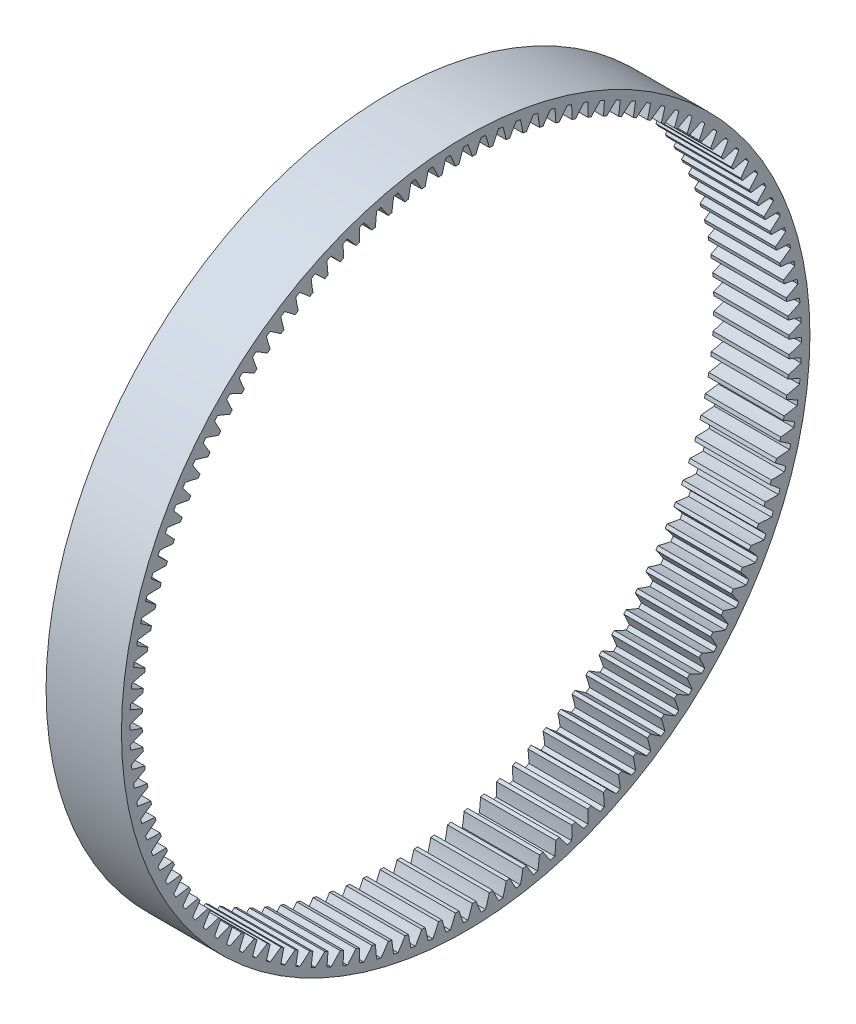
SolidWorks part; units mm, degrees
material "ABS"
ref_plane "Plane1" through (0, 0, 0) normal (0, 0, 1) x (1, 0, 0)
ref_plane "Plane2" through (0, 0, 0) normal (0, 1, 0) x (1, 0, 0)
ref_plane "Plane3" through (0, 0, 0) normal (1, 0, 0) x (0, 0, -1)
other "Configuration Table"
sketch "HoldingSke" plane through (0, 0, 0) normal (0, 1, 0) x (1, 0, 0)
  line L0 (0, 0) -> (-0.5, -0.866)
  line L1 (-15, 0) -> (100, 0) construction
  line L2 (0, 0) -> (-2.1039, 2.3779)
  line L3 (0, 0) -> (-11.863, 4.5341)
  line L4 (0, 0) -> (-4.318, 7.479)
  line L5 (0, 0) -> (-23.7986, -8.8762)
  line L6 (0, 0) -> (-10.5278, -7.1032)
  line L7 (-2.1039, 2.3779) -> (3.3635, 27.1825)
  line L8 (-76.2, 3.3779) -> (-54.61, 3.3779)
  line L9 (-71.009, 38.7566) -> (-53.1078, 45.2721)
  line L10 (-76.2, 71.12) -> (104.1128, 71.12)
  line L11 (0, 0) -> (-6, 0)
  line L12 (-76.2, 101.6) -> (-76.162, 101.6)
  line L13 (24.9733, 27.94) -> (52.9518, 28.4284)
  line L14 (24.9733, 27.94) -> (24.9743, 27.94)
  line L15 (24.9733, 27.94) -> (100.4006, 29.5858)
  circle A0 centre (0, 0) radius 18
  circle A1 centre (0, 0) radius 12.7
  circle A2 centre (0, 0) radius 12.7
  dimension "MHD" = 25.4
  dimension "Hub_dia" = 25.4
  dimension "Diameter" = 36
  dimension "Num_teeth" = 120
  dimension "Pitch" = 1
  dimension "Overall_len" = 25.4
  dimension "Show_teeth" = 120
  dimension "Thickness" = 12.7
  dimension "OAL" = 25.4001
  dimension "T_dim" = 21.59
  dimension "Ap" = 20
  dimension "H" = 19.05
  dimension "Pitch_radius" = 180.3128
  dimension "Width" = 6
  dimension "Backlash" = 0.038
  dimension "Addendum_fac" = 1
  dimension "Dedendum_fac" = 1.25
  dimension "Clearance_fac" = 0.25
  dimension "Dedendum_add" = 0.001
  dimension "Module" = 1
sketch "BasProSke" plane through (0, 0, 0) normal (0, 1, 0) x (1, 0, 0)
  line L0 (-10, 0) -> (60, 0) construction
  line L1 (0, 59) -> (0, 61.2764)
  line L2 (0, 59) -> (6, 59)
  line L3 (6, 59) -> (6, 61.2764)
  line L4 (6, 61.2764) -> (0, 61.2764)
  dimension "Thickness" = 6
  dimension "Diameter" = 122.5528
  dimension "Inside_diameter" = 118
revolve "Base-Revolve" add sketch "BasProSke" angle 360 about L0
sketch "TooCutSke" plane through (0, 0, 0) normal (1, 0, 0) x (0, 0, -1)
  line L3 (0.8804, 59.9935) -> (0.8804, 53.6633) construction
  line L4 (0, 0) -> (0, 59.563) construction
  line L5 (0, 0) -> (-1.7886, 68.3041) construction
  line L6 (-27.4212, 50.0427) -> (36.5015, 51.7166) construction
  circle A0 centre (0, 0) radius 60 construction
  circle A1 centre (0, 0) radius 61.251 construction
  circle A2 centre (0, 0) radius 50.7434 construction
  circle A3 centre (0, 0) radius 58.9746 construction
  arc A4 (1.2222, 58.9619) -> (0.4069, 61.2496) centre (-27.4212, 50.0427) ccw
  arc A5 (1.2222, 58.9619) -> (-1.2222, 58.9619) centre (0, 0) ccw
  arc A6 (0.4069, 61.2496) -> (-0.4069, 61.2496) centre (0, 0) ccw
  arc A7 (-0.4069, 61.2496) -> (-1.2222, 58.9619) centre (27.4212, 50.0427) ccw
  dimension "Pitch_dia" = 120
  dimension "Base_dia" = 101.4868
  dimension "Root_dia" = 122.502
  dimension "Overcut_dia" = 117.9492
  dimension "Flank_rad" = 30
  dimension "Half_ang" = 1.5
  dimension "Half_CT" = 0.8804
extrude "ToothCut" cut sketch "TooCutSke" along normal through all
fillet "Breaks" [suppressed] radius 0.1
fillet "RootFillets" [suppressed] radius 0.251
pattern_circular "TeethCuts" count 120 every 3 about axis through (-10, 0, 0) along (1, 0, 0) of "RootFillets", "Breaks", "ToothCut"
sketch "Sketch1" plane through (6, 0, 0) normal (1, 0, 0) x (0, 0, -1)
  circle A0 centre (0, 0) radius 61.2764 construction
  circle A1 centre (0, 0) radius 61.2764
  circle A2 centre (0, 0) radius 62.7764
  dimension "D1" = 1.5
extrude "Boss-Extrude1" add sketch "Sketch1" against normal up to surface (6 mm away) up to face at (0, 0, 61.2764)
sketch "Sketch3" plane through (0, 0, 0) normal (-1, 0, 0) x (0, 0, 1)
  circle A0 centre (0, 0) radius 62.7764 construction
  circle A1 centre (0, 0) radius 62.7764
  arc A480 (-1.8746, 58.9702) -> (-2.7992, 61.187) centre (-30.0027, 48.539) ccw
  arc A481 (-1.2142, 58.9875) -> (-1.8746, 58.9702) centre (0, 0) ccw
  arc A482 (-0.4069, 61.2496) -> (-1.2142, 58.9875) centre (27.4212, 50.0427) ccw
  arc A483 (0.4069, 61.2496) -> (-0.4069, 61.2496) centre (0, 0) ccw
  arc A484 (1.2142, 58.9875) -> (0.4069, 61.2496) centre (-27.4212, 50.0427) ccw
  arc A485 (1.8746, 58.9702) -> (1.2142, 58.9875) centre (0, 0) ccw
  arc A486 (2.7992, 61.187) -> (1.8746, 58.9702) centre (30.0027, 48.539) ccw
  arc A487 (3.6119, 61.1444) -> (2.7992, 61.187) centre (0, 0) ccw
  arc A488 (4.2997, 58.8431) -> (3.6119, 61.1444) centre (-24.7646, 51.4093) ccw
  arc A489 (4.9583, 58.7913) -> (4.2997, 58.8431) centre (0, 0) ccw
  arc A490 (5.9977, 60.9566) -> (4.9583, 58.7913) centre (32.5019, 46.9023) ccw
  arc A491 (6.807, 60.8716) -> (5.9977, 60.9566) centre (0, 0) ccw
  arc A492 (7.3735, 58.5374) -> (6.807, 60.8716) centre (-22.0401, 52.6349) ccw
  arc A493 (8.0284, 58.4512) -> (7.3735, 58.5374) centre (0, 0) ccw
  arc A494 (9.1797, 60.5592) -> (8.0284, 58.4512) centre (34.9121, 45.137) ccw
  arc A495 (9.9834, 60.4319) -> (9.1797, 60.5592) centre (0, 0) ccw
  arc A496 (10.427, 58.0713) -> (9.9834, 60.4319) centre (-19.2552, 53.7163) ccw
  arc A497 (11.0765, 57.9509) -> (10.427, 58.0713) centre (0, 0) ccw
  arc A498 (12.3365, 59.9958) -> (11.0765, 57.9509) centre (37.2265, 43.248) ccw
  arc A499 (13.1325, 59.8266) -> (12.3365, 59.9958) centre (0, 0) ccw
  arc A500 (13.4519, 57.446) -> (13.1325, 59.8266) centre (-16.4176, 54.6504) ccw
  arc A501 (14.0942, 57.2918) -> (13.4519, 57.446) centre (0, 0) ccw
  arc A502 (15.4595, 59.2679) -> (14.0942, 57.2918) centre (39.4389, 41.2404) ccw
  arc A503 (16.2456, 59.0573) -> (15.4595, 59.2679) centre (0, 0) ccw
  arc A504 (16.44, 56.6633) -> (16.2456, 59.0573) centre (-13.5349, 55.4347) ccw
  arc A505 (17.0733, 56.4757) -> (16.44, 56.6633) centre (0, 0) ccw
  arc A506 (18.5402, 58.3776) -> (17.0733, 56.4757) centre (41.5432, 39.1198) ccw
  arc A507 (19.3142, 58.1261) -> (18.5402, 58.3776) centre (0, 0) ccw
  arc A508 (19.383, 55.7252) -> (19.3142, 58.1261) centre (-10.6151, 56.0671) ccw
  arc A509 (20.0056, 55.5047) -> (19.383, 55.7252) centre (0, 0) ccw
  arc A510 (21.57, 57.3273) -> (20.0056, 55.5047) centre (43.5337, 36.892) ccw
  arc A511 (22.3298, 57.0357) -> (21.57, 57.3273) centre (0, 0) ccw
  arc A512 (22.2728, 54.6344) -> (22.3298, 57.0357) centre (-7.6662, 56.5458) ccw
  arc A513 (22.8831, 54.3816) -> (22.2728, 54.6344) centre (0, 0) ccw
  arc A514 (24.5408, 56.1198) -> (22.8831, 54.3816) centre (45.4048, 34.5631) ccw
  arc A515 (25.2842, 55.7888) -> (24.5408, 56.1198) centre (0, 0) ccw
  arc A516 (25.1016, 53.3939) -> (25.2842, 55.7888) centre (-4.6963, 56.8695) ccw
  arc A517 (25.6979, 53.1095) -> (25.1016, 53.3939) centre (0, 0) ccw
  arc A518 (27.4442, 54.7586) -> (25.6979, 53.1095) centre (47.1514, 32.1394) ccw
  arc A519 (28.1693, 54.3891) -> (27.4442, 54.7586) centre (0, 0) ccw
  arc A520 (27.8617, 52.007) -> (28.1693, 54.3891) centre (-1.7136, 57.0374) ccw
  arc A521 (28.4422, 51.6918) -> (27.8617, 52.007) centre (0, 0) ccw
  arc A522 (30.2724, 53.2472) -> (28.4422, 51.6918) centre (48.7689, 29.6277) ccw
  arc A523 (30.9772, 52.8403) -> (30.2724, 53.2472) centre (0, 0) ccw
  arc A524 (30.5453, 50.4776) -> (30.9772, 52.8403) centre (1.2739, 57.0489) ccw
  arc A525 (31.1085, 50.1324) -> (30.5453, 50.4776) centre (0, 0) ccw
  arc A526 (33.0177, 51.5899) -> (31.1085, 50.1324) centre (50.2526, 27.0347) ccw
  arc A527 (33.7002, 51.1467) -> (33.0177, 51.5899) centre (0, 0) ccw
  arc A528 (33.1452, 48.8098) -> (33.7002, 51.1467) centre (4.2578, 56.9041) ccw
  arc A529 (33.6896, 48.4356) -> (33.1452, 48.8098) centre (0, 0) ccw
  arc A530 (35.6725, 49.7912) -> (33.6896, 48.4356) centre (51.5986, 24.3676) ccw
  arc A531 (36.3308, 49.3128) -> (35.6725, 49.7912) centre (0, 0) ccw
  arc A532 (35.6543, 47.0082) -> (36.3308, 49.3128) centre (7.2301, 56.6032) ccw
  arc A533 (36.1784, 46.6061) -> (35.6543, 47.0082) centre (0, 0) ccw
  arc A534 (38.2294, 47.856) -> (36.1784, 46.6061) centre (52.8032, 21.6338) ccw
  arc A535 (38.8619, 47.3438) -> (38.2294, 47.856) centre (0, 0) ccw
  arc A536 (38.0657, 45.0778) -> (38.8619, 47.3438) centre (10.1826, 56.1473) ccw
  arc A537 (38.568, 44.6487) -> (38.0657, 45.0778) centre (0, 0) ccw
  arc A538 (40.6816, 45.7896) -> (38.568, 44.6487) centre (53.8631, 18.8406) ccw
  arc A539 (41.2864, 45.2451) -> (40.6816, 45.7896) centre (0, 0) ccw
  arc A540 (40.3727, 43.0238) -> (41.2864, 45.2451) centre (13.1072, 55.5374) ccw
  arc A541 (40.8519, 42.5691) -> (40.3727, 43.0238) centre (0, 0) ccw
  arc A542 (43.0223, 43.5978) -> (40.8519, 42.5691) centre (54.7753, 15.9958) ccw
  arc A543 (43.5978, 43.0223) -> (43.0223, 43.5978) centre (0, 0) ccw
  arc A544 (42.5691, 40.8519) -> (43.5978, 43.0223) centre (15.9958, 54.7753) ccw
  arc A545 (43.0238, 40.3727) -> (42.5691, 40.8519) centre (0, 0) ccw
  arc A546 (45.2451, 41.2864) -> (43.0238, 40.3727) centre (55.5374, 13.1072) ccw
  arc A547 (45.7896, 40.6816) -> (45.2451, 41.2864) centre (0, 0) ccw
  arc A548 (44.6487, 38.568) -> (45.7896, 40.6816) centre (18.8406, 53.8631) ccw
  arc A549 (45.0778, 38.0657) -> (44.6487, 38.568) centre (0, 0) ccw
  arc A550 (47.3438, 38.8619) -> (45.0778, 38.0657) centre (56.1473, 10.1826) ccw
  arc A551 (47.856, 38.2294) -> (47.3438, 38.8619) centre (0, 0) ccw
  arc A552 (46.6061, 36.1784) -> (47.856, 38.2294) centre (21.6338, 52.8032) ccw
  arc A553 (47.0082, 35.6543) -> (46.6061, 36.1784) centre (0, 0) ccw
  arc A554 (49.3128, 36.3308) -> (47.0082, 35.6543) centre (56.6032, 7.2301) ccw
  arc A555 (49.7912, 35.6725) -> (49.3128, 36.3308) centre (0, 0) ccw
  arc A556 (48.4356, 33.6896) -> (49.7912, 35.6725) centre (24.3676, 51.5986) ccw
  arc A557 (48.8098, 33.1452) -> (48.4356, 33.6896) centre (0, 0) ccw
  arc A558 (51.1467, 33.7002) -> (48.8098, 33.1452) centre (56.9041, 4.2578) ccw
  arc A559 (51.5899, 33.0177) -> (51.1467, 33.7002) centre (0, 0) ccw
  arc A560 (50.1324, 31.1085) -> (51.5899, 33.0177) centre (27.0347, 50.2526) ccw
  arc A561 (50.4776, 30.5453) -> (50.1324, 31.1085) centre (0, 0) ccw
  arc A562 (52.8403, 30.9772) -> (50.4776, 30.5453) centre (57.0489, 1.2739) ccw
  arc A563 (53.2472, 30.2724) -> (52.8403, 30.9772) centre (0, 0) ccw
  arc A564 (51.6918, 28.4422) -> (53.2472, 30.2724) centre (29.6277, 48.7689) ccw
  arc A565 (52.007, 27.8617) -> (51.6918, 28.4422) centre (0, 0) ccw
  arc A566 (54.3891, 28.1693) -> (52.007, 27.8617) centre (57.0374, -1.7136) ccw
  arc A567 (54.7586, 27.4442) -> (54.3891, 28.1693) centre (0, 0) ccw
  arc A568 (53.1095, 25.6979) -> (54.7586, 27.4442) centre (32.1394, 47.1514) ccw
  arc A569 (53.3939, 25.1016) -> (53.1095, 25.6979) centre (0, 0) ccw
  arc A570 (55.7888, 25.2842) -> (53.3939, 25.1016) centre (56.8695, -4.6963) ccw
  arc A571 (56.1198, 24.5408) -> (55.7888, 25.2842) centre (0, 0) ccw
  arc A572 (54.3816, 22.8831) -> (56.1198, 24.5408) centre (34.5631, 45.4048) ccw
  arc A573 (54.6344, 22.2728) -> (54.3816, 22.8831) centre (0, 0) ccw
  arc A574 (57.0357, 22.3298) -> (54.6344, 22.2728) centre (56.5458, -7.6662) ccw
  arc A575 (57.3273, 21.57) -> (57.0357, 22.3298) centre (0, 0) ccw
  arc A576 (55.5047, 20.0056) -> (57.3273, 21.57) centre (36.892, 43.5337) ccw
  arc A577 (55.7252, 19.383) -> (55.5047, 20.0056) centre (0, 0) ccw
  arc A578 (58.1261, 19.3142) -> (55.7252, 19.383) centre (56.0671, -10.6151) ccw
  arc A579 (58.3776, 18.5402) -> (58.1261, 19.3142) centre (0, 0) ccw
  arc A580 (56.4757, 17.0733) -> (58.3776, 18.5402) centre (39.1198, 41.5432) ccw
  arc A581 (56.6633, 16.44) -> (56.4757, 17.0733) centre (0, 0) ccw
  arc A582 (59.0573, 16.2456) -> (56.6633, 16.44) centre (55.4347, -13.5349) ccw
  arc A583 (59.2679, 15.4595) -> (59.0573, 16.2456) centre (0, 0) ccw
  arc A584 (57.2918, 14.0942) -> (59.2679, 15.4595) centre (41.2404, 39.4389) ccw
  arc A585 (57.446, 13.4519) -> (57.2918, 14.0942) centre (0, 0) ccw
  arc A586 (59.8266, 13.1325) -> (57.446, 13.4519) centre (54.6504, -16.4176) ccw
  arc A587 (59.9958, 12.3365) -> (59.8266, 13.1325) centre (0, 0) ccw
  arc A588 (57.9509, 11.0765) -> (59.9958, 12.3365) centre (43.248, 37.2265) ccw
  arc A589 (58.0713, 10.427) -> (57.9509, 11.0765) centre (0, 0) ccw
  arc A590 (60.4319, 9.9834) -> (58.0713, 10.427) centre (53.7163, -19.2552) ccw
  arc A591 (60.5592, 9.1797) -> (60.4319, 9.9834) centre (0, 0) ccw
  arc A592 (58.4512, 8.0284) -> (60.5592, 9.1797) centre (45.137, 34.9121) ccw
  arc A593 (58.5374, 7.3735) -> (58.4512, 8.0284) centre (0, 0) ccw
  arc A594 (60.8716, 6.807) -> (58.5374, 7.3735) centre (52.6349, -22.0401) ccw
  arc A595 (60.9566, 5.9977) -> (60.8716, 6.807) centre (0, 0) ccw
  arc A596 (58.7913, 4.9583) -> (60.9566, 5.9977) centre (46.9023, 32.5019) ccw
  arc A597 (58.8431, 4.2997) -> (58.7913, 4.9583) centre (0, 0) ccw
  arc A598 (61.1444, 3.6119) -> (58.8431, 4.2997) centre (51.4093, -24.7646) ccw
  arc A599 (61.187, 2.7992) -> (61.1444, 3.6119) centre (0, 0) ccw
  arc A600 (58.9702, 1.8746) -> (61.187, 2.7992) centre (48.539, 30.0027) ccw
  arc A601 (58.9875, 1.2142) -> (58.9702, 1.8746) centre (0, 0) ccw
  arc A602 (61.2496, 0.4069) -> (58.9875, 1.2142) centre (50.0427, -27.4212) ccw
  arc A603 (61.2496, -0.4069) -> (61.2496, 0.4069) centre (0, 0) ccw
  arc A604 (58.9875, -1.2142) -> (61.2496, -0.4069) centre (50.0427, 27.4212) ccw
  arc A605 (58.9702, -1.8746) -> (58.9875, -1.2142) centre (0, 0) ccw
  arc A606 (61.187, -2.7992) -> (58.9702, -1.8746) centre (48.539, -30.0027) ccw
  arc A607 (61.1444, -3.6119) -> (61.187, -2.7992) centre (0, 0) ccw
  arc A608 (58.8431, -4.2997) -> (61.1444, -3.6119) centre (51.4093, 24.7646) ccw
  arc A609 (58.7913, -4.9583) -> (58.8431, -4.2997) centre (0, 0) ccw
  arc A610 (60.9566, -5.9977) -> (58.7913, -4.9583) centre (46.9023, -32.5019) ccw
  arc A611 (60.8716, -6.807) -> (60.9566, -5.9977) centre (0, 0) ccw
  arc A612 (58.5374, -7.3735) -> (60.8716, -6.807) centre (52.6349, 22.0401) ccw
  arc A613 (58.4512, -8.0284) -> (58.5374, -7.3735) centre (0, 0) ccw
  arc A614 (60.5592, -9.1797) -> (58.4512, -8.0284) centre (45.137, -34.9121) ccw
  arc A615 (60.4319, -9.9834) -> (60.5592, -9.1797) centre (0, 0) ccw
  arc A616 (58.0713, -10.427) -> (60.4319, -9.9834) centre (53.7163, 19.2552) ccw
  arc A617 (57.9509, -11.0765) -> (58.0713, -10.427) centre (0, 0) ccw
  arc A618 (59.9958, -12.3365) -> (57.9509, -11.0765) centre (43.248, -37.2265) ccw
  arc A619 (59.8266, -13.1325) -> (59.9958, -12.3365) centre (0, 0) ccw
  arc A620 (57.446, -13.4519) -> (59.8266, -13.1325) centre (54.6504, 16.4176) ccw
  arc A621 (57.2918, -14.0942) -> (57.446, -13.4519) centre (0, 0) ccw
  arc A622 (59.2679, -15.4595) -> (57.2918, -14.0942) centre (41.2404, -39.4389) ccw
  arc A623 (59.0573, -16.2456) -> (59.2679, -15.4595) centre (0, 0) ccw
  arc A624 (56.6633, -16.44) -> (59.0573, -16.2456) centre (55.4347, 13.5349) ccw
  arc A625 (56.4757, -17.0733) -> (56.6633, -16.44) centre (0, 0) ccw
  arc A626 (58.3776, -18.5402) -> (56.4757, -17.0733) centre (39.1198, -41.5432) ccw
  arc A627 (58.1261, -19.3142) -> (58.3776, -18.5402) centre (0, 0) ccw
  arc A628 (55.7252, -19.383) -> (58.1261, -19.3142) centre (56.0671, 10.6151) ccw
  arc A629 (55.5047, -20.0056) -> (55.7252, -19.383) centre (0, 0) ccw
  arc A630 (57.3273, -21.57) -> (55.5047, -20.0056) centre (36.892, -43.5337) ccw
  arc A631 (57.0357, -22.3298) -> (57.3273, -21.57) centre (0, 0) ccw
  arc A632 (54.6344, -22.2728) -> (57.0357, -22.3298) centre (56.5458, 7.6662) ccw
  arc A633 (54.3816, -22.8831) -> (54.6344, -22.2728) centre (0, 0) ccw
  arc A634 (56.1198, -24.5408) -> (54.3816, -22.8831) centre (34.5631, -45.4048) ccw
  arc A635 (55.7888, -25.2842) -> (56.1198, -24.5408) centre (0, 0) ccw
  arc A636 (53.3939, -25.1016) -> (55.7888, -25.2842) centre (56.8695, 4.6963) ccw
  arc A637 (53.1095, -25.6979) -> (53.3939, -25.1016) centre (0, 0) ccw
  arc A638 (54.7586, -27.4442) -> (53.1095, -25.6979) centre (32.1394, -47.1514) ccw
  arc A639 (54.3891, -28.1693) -> (54.7586, -27.4442) centre (0, 0) ccw
  arc A640 (52.007, -27.8617) -> (54.3891, -28.1693) centre (57.0374, 1.7136) ccw
  arc A641 (51.6918, -28.4422) -> (52.007, -27.8617) centre (0, 0) ccw
  arc A642 (53.2472, -30.2724) -> (51.6918, -28.4422) centre (29.6277, -48.7689) ccw
  arc A643 (52.8403, -30.9772) -> (53.2472, -30.2724) centre (0, 0) ccw
  arc A644 (50.4776, -30.5453) -> (52.8403, -30.9772) centre (57.0489, -1.2739) ccw
  arc A645 (50.1324, -31.1085) -> (50.4776, -30.5453) centre (0, 0) ccw
  arc A646 (51.5899, -33.0177) -> (50.1324, -31.1085) centre (27.0347, -50.2526) ccw
  arc A647 (51.1467, -33.7002) -> (51.5899, -33.0177) centre (0, 0) ccw
  arc A648 (48.8098, -33.1452) -> (51.1467, -33.7002) centre (56.9041, -4.2578) ccw
  arc A649 (48.4356, -33.6896) -> (48.8098, -33.1452) centre (0, 0) ccw
  arc A650 (49.7912, -35.6725) -> (48.4356, -33.6896) centre (24.3676, -51.5986) ccw
  arc A651 (49.3128, -36.3308) -> (49.7912, -35.6725) centre (0, 0) ccw
  arc A652 (47.0082, -35.6543) -> (49.3128, -36.3308) centre (56.6032, -7.2301) ccw
  arc A653 (46.6061, -36.1784) -> (47.0082, -35.6543) centre (0, 0) ccw
  arc A654 (47.856, -38.2294) -> (46.6061, -36.1784) centre (21.6338, -52.8032) ccw
  arc A655 (47.3438, -38.8619) -> (47.856, -38.2294) centre (0, 0) ccw
  arc A656 (45.0778, -38.0657) -> (47.3438, -38.8619) centre (56.1473, -10.1826) ccw
  arc A657 (44.6487, -38.568) -> (45.0778, -38.0657) centre (0, 0) ccw
  arc A658 (45.7896, -40.6816) -> (44.6487, -38.568) centre (18.8406, -53.8631) ccw
  arc A659 (45.2451, -41.2864) -> (45.7896, -40.6816) centre (0, 0) ccw
  arc A660 (43.0238, -40.3727) -> (45.2451, -41.2864) centre (55.5374, -13.1072) ccw
  arc A661 (42.5691, -40.8519) -> (43.0238, -40.3727) centre (0, 0) ccw
  arc A662 (43.5978, -43.0223) -> (42.5691, -40.8519) centre (15.9958, -54.7753) ccw
  arc A663 (43.0223, -43.5978) -> (43.5978, -43.0223) centre (0, 0) ccw
  arc A664 (40.8519, -42.5691) -> (43.0223, -43.5978) centre (54.7753, -15.9958) ccw
  arc A665 (40.3727, -43.0238) -> (40.8519, -42.5691) centre (0, 0) ccw
  arc A666 (41.2864, -45.2451) -> (40.3727, -43.0238) centre (13.1072, -55.5374) ccw
  arc A667 (40.6816, -45.7896) -> (41.2864, -45.2451) centre (0, 0) ccw
  arc A668 (38.568, -44.6487) -> (40.6816, -45.7896) centre (53.8631, -18.8406) ccw
  arc A669 (38.0657, -45.0778) -> (38.568, -44.6487) centre (0, 0) ccw
  arc A670 (38.8619, -47.3438) -> (38.0657, -45.0778) centre (10.1826, -56.1473) ccw
  arc A671 (38.2294, -47.856) -> (38.8619, -47.3438) centre (0, 0) ccw
  arc A672 (36.1784, -46.6061) -> (38.2294, -47.856) centre (52.8032, -21.6338) ccw
  arc A673 (35.6543, -47.0082) -> (36.1784, -46.6061) centre (0, 0) ccw
  arc A674 (36.3308, -49.3128) -> (35.6543, -47.0082) centre (7.2301, -56.6032) ccw
  arc A675 (35.6725, -49.7912) -> (36.3308, -49.3128) centre (0, 0) ccw
  arc A676 (33.6896, -48.4356) -> (35.6725, -49.7912) centre (51.5986, -24.3676) ccw
  arc A677 (33.1452, -48.8098) -> (33.6896, -48.4356) centre (0, 0) ccw
  arc A678 (33.7002, -51.1467) -> (33.1452, -48.8098) centre (4.2578, -56.9041) ccw
  arc A679 (33.0177, -51.5899) -> (33.7002, -51.1467) centre (0, 0) ccw
  arc A680 (31.1085, -50.1324) -> (33.0177, -51.5899) centre (50.2526, -27.0347) ccw
  arc A681 (30.5453, -50.4776) -> (31.1085, -50.1324) centre (0, 0) ccw
  arc A682 (30.9772, -52.8403) -> (30.5453, -50.4776) centre (1.2739, -57.0489) ccw
  arc A683 (30.2724, -53.2472) -> (30.9772, -52.8403) centre (0, 0) ccw
  arc A684 (28.4422, -51.6918) -> (30.2724, -53.2472) centre (48.7689, -29.6277) ccw
  arc A685 (27.8617, -52.007) -> (28.4422, -51.6918) centre (0, 0) ccw
  arc A686 (28.1693, -54.3891) -> (27.8617, -52.007) centre (-1.7136, -57.0374) ccw
  arc A687 (27.4442, -54.7586) -> (28.1693, -54.3891) centre (0, 0) ccw
  arc A688 (25.6979, -53.1095) -> (27.4442, -54.7586) centre (47.1514, -32.1394) ccw
  arc A689 (25.1016, -53.3939) -> (25.6979, -53.1095) centre (0, 0) ccw
  arc A690 (25.2842, -55.7888) -> (25.1016, -53.3939) centre (-4.6963, -56.8695) ccw
  arc A691 (24.5408, -56.1198) -> (25.2842, -55.7888) centre (0, 0) ccw
  arc A692 (22.8831, -54.3816) -> (24.5408, -56.1198) centre (45.4048, -34.5631) ccw
  arc A693 (22.2728, -54.6344) -> (22.8831, -54.3816) centre (0, 0) ccw
  arc A694 (22.3298, -57.0357) -> (22.2728, -54.6344) centre (-7.6662, -56.5458) ccw
  arc A695 (21.57, -57.3273) -> (22.3298, -57.0357) centre (0, 0) ccw
  arc A696 (20.0056, -55.5047) -> (21.57, -57.3273) centre (43.5337, -36.892) ccw
  arc A697 (19.383, -55.7252) -> (20.0056, -55.5047) centre (0, 0) ccw
  arc A698 (19.3142, -58.1261) -> (19.383, -55.7252) centre (-10.6151, -56.0671) ccw
  arc A699 (18.5402, -58.3776) -> (19.3142, -58.1261) centre (0, 0) ccw
  arc A700 (17.0733, -56.4757) -> (18.5402, -58.3776) centre (41.5432, -39.1198) ccw
  arc A701 (16.44, -56.6633) -> (17.0733, -56.4757) centre (0, 0) ccw
  arc A702 (16.2456, -59.0573) -> (16.44, -56.6633) centre (-13.5349, -55.4347) ccw
  arc A703 (15.4595, -59.2679) -> (16.2456, -59.0573) centre (0, 0) ccw
  arc A704 (14.0942, -57.2918) -> (15.4595, -59.2679) centre (39.4389, -41.2404) ccw
  arc A705 (13.4519, -57.446) -> (14.0942, -57.2918) centre (0, 0) ccw
  arc A706 (13.1325, -59.8266) -> (13.4519, -57.446) centre (-16.4176, -54.6504) ccw
  arc A707 (12.3365, -59.9958) -> (13.1325, -59.8266) centre (0, 0) ccw
  arc A708 (11.0765, -57.9509) -> (12.3365, -59.9958) centre (37.2265, -43.248) ccw
  arc A709 (10.427, -58.0713) -> (11.0765, -57.9509) centre (0, 0) ccw
  arc A710 (9.9834, -60.4319) -> (10.427, -58.0713) centre (-19.2552, -53.7163) ccw
  arc A711 (9.1797, -60.5592) -> (9.9834, -60.4319) centre (0, 0) ccw
  arc A712 (8.0284, -58.4512) -> (9.1797, -60.5592) centre (34.9121, -45.137) ccw
  arc A713 (7.3735, -58.5374) -> (8.0284, -58.4512) centre (0, 0) ccw
  arc A714 (6.807, -60.8716) -> (7.3735, -58.5374) centre (-22.0401, -52.6349) ccw
  arc A715 (5.9977, -60.9566) -> (6.807, -60.8716) centre (0, 0) ccw
  arc A716 (4.9583, -58.7913) -> (5.9977, -60.9566) centre (32.5019, -46.9023) ccw
  arc A717 (4.2997, -58.8431) -> (4.9583, -58.7913) centre (0, 0) ccw
  arc A718 (3.6119, -61.1444) -> (4.2997, -58.8431) centre (-24.7646, -51.4093) ccw
  arc A719 (2.7992, -61.187) -> (3.6119, -61.1444) centre (0, 0) ccw
  arc A720 (1.8746, -58.9702) -> (2.7992, -61.187) centre (30.0027, -48.539) ccw
  arc A721 (1.2142, -58.9875) -> (1.8746, -58.9702) centre (0, 0) ccw
  arc A722 (0.4069, -61.2496) -> (1.2142, -58.9875) centre (-27.4212, -50.0427) ccw
  arc A723 (-0.4069, -61.2496) -> (0.4069, -61.2496) centre (0, 0) ccw
  arc A724 (-1.2142, -58.9875) -> (-0.4069, -61.2496) centre (27.4212, -50.0427) ccw
  arc A725 (-1.8746, -58.9702) -> (-1.2142, -58.9875) centre (0, 0) ccw
  arc A726 (-2.7992, -61.187) -> (-1.8746, -58.9702) centre (-30.0027, -48.539) ccw
  arc A727 (-3.6119, -61.1444) -> (-2.7992, -61.187) centre (0, 0) ccw
  arc A728 (-4.2997, -58.8431) -> (-3.6119, -61.1444) centre (24.7646, -51.4093) ccw
  arc A729 (-4.9583, -58.7913) -> (-4.2997, -58.8431) centre (0, 0) ccw
  arc A730 (-5.9977, -60.9566) -> (-4.9583, -58.7913) centre (-32.5019, -46.9023) ccw
  arc A731 (-6.807, -60.8716) -> (-5.9977, -60.9566) centre (0, 0) ccw
  arc A732 (-7.3735, -58.5374) -> (-6.807, -60.8716) centre (22.0401, -52.6349) ccw
  arc A733 (-8.0284, -58.4512) -> (-7.3735, -58.5374) centre (0, 0) ccw
  arc A734 (-9.1797, -60.5592) -> (-8.0284, -58.4512) centre (-34.9121, -45.137) ccw
  arc A735 (-9.9834, -60.4319) -> (-9.1797, -60.5592) centre (0, 0) ccw
  arc A736 (-10.427, -58.0713) -> (-9.9834, -60.4319) centre (19.2552, -53.7163) ccw
  arc A737 (-11.0765, -57.9509) -> (-10.427, -58.0713) centre (0, 0) ccw
  arc A738 (-12.3365, -59.9958) -> (-11.0765, -57.9509) centre (-37.2265, -43.248) ccw
  arc A739 (-13.1325, -59.8266) -> (-12.3365, -59.9958) centre (0, 0) ccw
  arc A740 (-13.4519, -57.446) -> (-13.1325, -59.8266) centre (16.4176, -54.6504) ccw
  arc A741 (-14.0942, -57.2918) -> (-13.4519, -57.446) centre (0, 0) ccw
  arc A742 (-15.4595, -59.2679) -> (-14.0942, -57.2918) centre (-39.4389, -41.2404) ccw
  arc A743 (-16.2456, -59.0573) -> (-15.4595, -59.2679) centre (0, 0) ccw
  arc A744 (-16.44, -56.6633) -> (-16.2456, -59.0573) centre (13.5349, -55.4347) ccw
  arc A745 (-17.0733, -56.4757) -> (-16.44, -56.6633) centre (0, 0) ccw
  arc A746 (-18.5402, -58.3776) -> (-17.0733, -56.4757) centre (-41.5432, -39.1198) ccw
  arc A747 (-19.3142, -58.1261) -> (-18.5402, -58.3776) centre (0, 0) ccw
  arc A748 (-19.383, -55.7252) -> (-19.3142, -58.1261) centre (10.6151, -56.0671) ccw
  arc A749 (-20.0056, -55.5047) -> (-19.383, -55.7252) centre (0, 0) ccw
  arc A750 (-21.57, -57.3273) -> (-20.0056, -55.5047) centre (-43.5337, -36.892) ccw
  arc A751 (-22.3298, -57.0357) -> (-21.57, -57.3273) centre (0, 0) ccw
  arc A752 (-22.2728, -54.6344) -> (-22.3298, -57.0357) centre (7.6662, -56.5458) ccw
  arc A753 (-22.8831, -54.3816) -> (-22.2728, -54.6344) centre (0, 0) ccw
  arc A754 (-24.5408, -56.1198) -> (-22.8831, -54.3816) centre (-45.4048, -34.5631) ccw
  arc A755 (-25.2842, -55.7888) -> (-24.5408, -56.1198) centre (0, 0) ccw
  arc A756 (-25.1016, -53.3939) -> (-25.2842, -55.7888) centre (4.6963, -56.8695) ccw
  arc A757 (-25.6979, -53.1095) -> (-25.1016, -53.3939) centre (0, 0) ccw
  arc A758 (-27.4442, -54.7586) -> (-25.6979, -53.1095) centre (-47.1514, -32.1394) ccw
  arc A759 (-28.1693, -54.3891) -> (-27.4442, -54.7586) centre (0, 0) ccw
  arc A760 (-27.8617, -52.007) -> (-28.1693, -54.3891) centre (1.7136, -57.0374) ccw
  arc A761 (-28.4422, -51.6918) -> (-27.8617, -52.007) centre (0, 0) ccw
  arc A762 (-30.2724, -53.2472) -> (-28.4422, -51.6918) centre (-48.7689, -29.6277) ccw
  arc A763 (-30.9772, -52.8403) -> (-30.2724, -53.2472) centre (0, 0) ccw
  arc A764 (-30.5453, -50.4776) -> (-30.9772, -52.8403) centre (-1.2739, -57.0489) ccw
  arc A765 (-31.1085, -50.1324) -> (-30.5453, -50.4776) centre (0, 0) ccw
  arc A766 (-33.0177, -51.5899) -> (-31.1085, -50.1324) centre (-50.2526, -27.0347) ccw
  arc A767 (-33.7002, -51.1467) -> (-33.0177, -51.5899) centre (0, 0) ccw
  arc A768 (-33.1452, -48.8098) -> (-33.7002, -51.1467) centre (-4.2578, -56.9041) ccw
  arc A769 (-33.6896, -48.4356) -> (-33.1452, -48.8098) centre (0, 0) ccw
  arc A770 (-35.6725, -49.7912) -> (-33.6896, -48.4356) centre (-51.5986, -24.3676) ccw
  arc A771 (-36.3308, -49.3128) -> (-35.6725, -49.7912) centre (0, 0) ccw
  arc A772 (-35.6543, -47.0082) -> (-36.3308, -49.3128) centre (-7.2301, -56.6032) ccw
  arc A773 (-36.1784, -46.6061) -> (-35.6543, -47.0082) centre (0, 0) ccw
  arc A774 (-38.2294, -47.856) -> (-36.1784, -46.6061) centre (-52.8032, -21.6338) ccw
  arc A775 (-38.8619, -47.3438) -> (-38.2294, -47.856) centre (0, 0) ccw
  arc A776 (-38.0657, -45.0778) -> (-38.8619, -47.3438) centre (-10.1826, -56.1473) ccw
  arc A777 (-38.568, -44.6487) -> (-38.0657, -45.0778) centre (0, 0) ccw
  arc A778 (-40.6816, -45.7896) -> (-38.568, -44.6487) centre (-53.8631, -18.8406) ccw
  arc A779 (-41.2864, -45.2451) -> (-40.6816, -45.7896) centre (0, 0) ccw
  arc A780 (-40.3727, -43.0238) -> (-41.2864, -45.2451) centre (-13.1072, -55.5374) ccw
  arc A781 (-40.8519, -42.5691) -> (-40.3727, -43.0238) centre (0, 0) ccw
  arc A782 (-43.0223, -43.5978) -> (-40.8519, -42.5691) centre (-54.7753, -15.9958) ccw
  arc A783 (-43.5978, -43.0223) -> (-43.0223, -43.5978) centre (0, 0) ccw
  arc A784 (-42.5691, -40.8519) -> (-43.5978, -43.0223) centre (-15.9958, -54.7753) ccw
  arc A785 (-43.0238, -40.3727) -> (-42.5691, -40.8519) centre (0, 0) ccw
  arc A786 (-45.2451, -41.2864) -> (-43.0238, -40.3727) centre (-55.5374, -13.1072) ccw
  arc A787 (-45.7896, -40.6816) -> (-45.2451, -41.2864) centre (0, 0) ccw
  arc A788 (-44.6487, -38.568) -> (-45.7896, -40.6816) centre (-18.8406, -53.8631) ccw
  arc A789 (-45.0778, -38.0657) -> (-44.6487, -38.568) centre (0, 0) ccw
  arc A790 (-47.3438, -38.8619) -> (-45.0778, -38.0657) centre (-56.1473, -10.1826) ccw
  arc A791 (-47.856, -38.2294) -> (-47.3438, -38.8619) centre (0, 0) ccw
  arc A792 (-46.6061, -36.1784) -> (-47.856, -38.2294) centre (-21.6338, -52.8032) ccw
  arc A793 (-47.0082, -35.6543) -> (-46.6061, -36.1784) centre (0, 0) ccw
  arc A794 (-49.3128, -36.3308) -> (-47.0082, -35.6543) centre (-56.6032, -7.2301) ccw
  arc A795 (-49.7912, -35.6725) -> (-49.3128, -36.3308) centre (0, 0) ccw
  arc A796 (-48.4356, -33.6896) -> (-49.7912, -35.6725) centre (-24.3676, -51.5986) ccw
  arc A797 (-48.8098, -33.1452) -> (-48.4356, -33.6896) centre (0, 0) ccw
  arc A798 (-51.1467, -33.7002) -> (-48.8098, -33.1452) centre (-56.9041, -4.2578) ccw
  arc A799 (-51.5899, -33.0177) -> (-51.1467, -33.7002) centre (0, 0) ccw
  arc A800 (-50.1324, -31.1085) -> (-51.5899, -33.0177) centre (-27.0347, -50.2526) ccw
  arc A801 (-50.4776, -30.5453) -> (-50.1324, -31.1085) centre (0, 0) ccw
  arc A802 (-52.8403, -30.9772) -> (-50.4776, -30.5453) centre (-57.0489, -1.2739) ccw
  arc A803 (-53.2472, -30.2724) -> (-52.8403, -30.9772) centre (0, 0) ccw
  arc A804 (-51.6918, -28.4422) -> (-53.2472, -30.2724) centre (-29.6277, -48.7689) ccw
  arc A805 (-52.007, -27.8617) -> (-51.6918, -28.4422) centre (0, 0) ccw
  arc A806 (-54.3891, -28.1693) -> (-52.007, -27.8617) centre (-57.0374, 1.7136) ccw
  arc A807 (-54.7586, -27.4442) -> (-54.3891, -28.1693) centre (0, 0) ccw
  arc A808 (-53.1095, -25.6979) -> (-54.7586, -27.4442) centre (-32.1394, -47.1514) ccw
  arc A809 (-53.3939, -25.1016) -> (-53.1095, -25.6979) centre (0, 0) ccw
  arc A810 (-55.7888, -25.2842) -> (-53.3939, -25.1016) centre (-56.8695, 4.6963) ccw
  arc A811 (-56.1198, -24.5408) -> (-55.7888, -25.2842) centre (0, 0) ccw
  arc A812 (-54.3816, -22.8831) -> (-56.1198, -24.5408) centre (-34.5631, -45.4048) ccw
  arc A813 (-54.6344, -22.2728) -> (-54.3816, -22.8831) centre (0, 0) ccw
  arc A814 (-57.0357, -22.3298) -> (-54.6344, -22.2728) centre (-56.5458, 7.6662) ccw
  arc A815 (-57.3273, -21.57) -> (-57.0357, -22.3298) centre (0, 0) ccw
  arc A816 (-55.5047, -20.0056) -> (-57.3273, -21.57) centre (-36.892, -43.5337) ccw
  arc A817 (-55.7252, -19.383) -> (-55.5047, -20.0056) centre (0, 0) ccw
  arc A818 (-58.1261, -19.3142) -> (-55.7252, -19.383) centre (-56.0671, 10.6151) ccw
  arc A819 (-58.3776, -18.5402) -> (-58.1261, -19.3142) centre (0, 0) ccw
  arc A820 (-56.4757, -17.0733) -> (-58.3776, -18.5402) centre (-39.1198, -41.5432) ccw
  arc A821 (-56.6633, -16.44) -> (-56.4757, -17.0733) centre (0, 0) ccw
  arc A822 (-59.0573, -16.2456) -> (-56.6633, -16.44) centre (-55.4347, 13.5349) ccw
  arc A823 (-59.2679, -15.4595) -> (-59.0573, -16.2456) centre (0, 0) ccw
  arc A824 (-57.2918, -14.0942) -> (-59.2679, -15.4595) centre (-41.2404, -39.4389) ccw
  arc A825 (-57.446, -13.4519) -> (-57.2918, -14.0942) centre (0, 0) ccw
  arc A826 (-59.8266, -13.1325) -> (-57.446, -13.4519) centre (-54.6504, 16.4176) ccw
  arc A827 (-59.9958, -12.3365) -> (-59.8266, -13.1325) centre (0, 0) ccw
  arc A828 (-57.9509, -11.0765) -> (-59.9958, -12.3365) centre (-43.248, -37.2265) ccw
  arc A829 (-58.0713, -10.427) -> (-57.9509, -11.0765) centre (0, 0) ccw
  arc A830 (-60.4319, -9.9834) -> (-58.0713, -10.427) centre (-53.7163, 19.2552) ccw
  arc A831 (-60.5592, -9.1797) -> (-60.4319, -9.9834) centre (0, 0) ccw
  arc A832 (-58.4512, -8.0284) -> (-60.5592, -9.1797) centre (-45.137, -34.9121) ccw
  arc A833 (-58.5374, -7.3735) -> (-58.4512, -8.0284) centre (0, 0) ccw
  arc A834 (-60.8716, -6.807) -> (-58.5374, -7.3735) centre (-52.6349, 22.0401) ccw
  arc A835 (-60.9566, -5.9977) -> (-60.8716, -6.807) centre (0, 0) ccw
  arc A836 (-58.7913, -4.9583) -> (-60.9566, -5.9977) centre (-46.9023, -32.5019) ccw
  arc A837 (-58.8431, -4.2997) -> (-58.7913, -4.9583) centre (0, 0) ccw
  arc A838 (-61.1444, -3.6119) -> (-58.8431, -4.2997) centre (-51.4093, 24.7646) ccw
  arc A839 (-61.187, -2.7992) -> (-61.1444, -3.6119) centre (0, 0) ccw
  arc A840 (-58.9702, -1.8746) -> (-61.187, -2.7992) centre (-48.539, -30.0027) ccw
  arc A841 (-58.9875, -1.2142) -> (-58.9702, -1.8746) centre (0, 0) ccw
  arc A842 (-61.2496, -0.4069) -> (-58.9875, -1.2142) centre (-50.0427, 27.4212) ccw
  arc A843 (-61.2496, 0.4069) -> (-61.2496, -0.4069) centre (0, 0) ccw
  arc A844 (-58.9875, 1.2142) -> (-61.2496, 0.4069) centre (-50.0427, -27.4212) ccw
  arc A845 (-58.9702, 1.8746) -> (-58.9875, 1.2142) centre (0, 0) ccw
  arc A846 (-61.187, 2.7992) -> (-58.9702, 1.8746) centre (-48.539, 30.0027) ccw
  arc A847 (-61.1444, 3.6119) -> (-61.187, 2.7992) centre (0, 0) ccw
  arc A848 (-58.8431, 4.2997) -> (-61.1444, 3.6119) centre (-51.4093, -24.7646) ccw
  arc A849 (-58.7913, 4.9583) -> (-58.8431, 4.2997) centre (0, 0) ccw
  arc A850 (-60.9566, 5.9977) -> (-58.7913, 4.9583) centre (-46.9023, 32.5019) ccw
  arc A851 (-60.8716, 6.807) -> (-60.9566, 5.9977) centre (0, 0) ccw
  arc A852 (-58.5374, 7.3735) -> (-60.8716, 6.807) centre (-52.6349, -22.0401) ccw
  arc A853 (-58.4512, 8.0284) -> (-58.5374, 7.3735) centre (0, 0) ccw
  arc A854 (-60.5592, 9.1797) -> (-58.4512, 8.0284) centre (-45.137, 34.9121) ccw
  arc A855 (-60.4319, 9.9834) -> (-60.5592, 9.1797) centre (0, 0) ccw
  arc A856 (-58.0713, 10.427) -> (-60.4319, 9.9834) centre (-53.7163, -19.2552) ccw
  arc A857 (-57.9509, 11.0765) -> (-58.0713, 10.427) centre (0, 0) ccw
  arc A858 (-59.9958, 12.3365) -> (-57.9509, 11.0765) centre (-43.248, 37.2265) ccw
  arc A859 (-59.8266, 13.1325) -> (-59.9958, 12.3365) centre (0, 0) ccw
  arc A860 (-57.446, 13.4519) -> (-59.8266, 13.1325) centre (-54.6504, -16.4176) ccw
  arc A861 (-57.2918, 14.0942) -> (-57.446, 13.4519) centre (0, 0) ccw
  arc A862 (-59.2679, 15.4595) -> (-57.2918, 14.0942) centre (-41.2404, 39.4389) ccw
  arc A863 (-59.0573, 16.2456) -> (-59.2679, 15.4595) centre (0, 0) ccw
  arc A864 (-56.6633, 16.44) -> (-59.0573, 16.2456) centre (-55.4347, -13.5349) ccw
  arc A865 (-56.4757, 17.0733) -> (-56.6633, 16.44) centre (0, 0) ccw
  arc A866 (-58.3776, 18.5402) -> (-56.4757, 17.0733) centre (-39.1198, 41.5432) ccw
  arc A867 (-58.1261, 19.3142) -> (-58.3776, 18.5402) centre (0, 0) ccw
  arc A868 (-55.7252, 19.383) -> (-58.1261, 19.3142) centre (-56.0671, -10.6151) ccw
  arc A869 (-55.5047, 20.0056) -> (-55.7252, 19.383) centre (0, 0) ccw
  arc A870 (-57.3273, 21.57) -> (-55.5047, 20.0056) centre (-36.892, 43.5337) ccw
  arc A871 (-57.0357, 22.3298) -> (-57.3273, 21.57) centre (0, 0) ccw
  arc A872 (-54.6344, 22.2728) -> (-57.0357, 22.3298) centre (-56.5458, -7.6662) ccw
  arc A873 (-54.3816, 22.8831) -> (-54.6344, 22.2728) centre (0, 0) ccw
  arc A874 (-56.1198, 24.5408) -> (-54.3816, 22.8831) centre (-34.5631, 45.4048) ccw
  arc A875 (-55.7888, 25.2842) -> (-56.1198, 24.5408) centre (0, 0) ccw
  arc A876 (-53.3939, 25.1016) -> (-55.7888, 25.2842) centre (-56.8695, -4.6963) ccw
  arc A877 (-53.1095, 25.6979) -> (-53.3939, 25.1016) centre (0, 0) ccw
  arc A878 (-54.7586, 27.4442) -> (-53.1095, 25.6979) centre (-32.1394, 47.1514) ccw
  arc A879 (-54.3891, 28.1693) -> (-54.7586, 27.4442) centre (0, 0) ccw
  arc A880 (-52.007, 27.8617) -> (-54.3891, 28.1693) centre (-57.0374, -1.7136) ccw
  arc A881 (-51.6918, 28.4422) -> (-52.007, 27.8617) centre (0, 0) ccw
  arc A882 (-53.2472, 30.2724) -> (-51.6918, 28.4422) centre (-29.6277, 48.7689) ccw
  arc A883 (-52.8403, 30.9772) -> (-53.2472, 30.2724) centre (0, 0) ccw
  arc A884 (-50.4776, 30.5453) -> (-52.8403, 30.9772) centre (-57.0489, 1.2739) ccw
  arc A885 (-50.1324, 31.1085) -> (-50.4776, 30.5453) centre (0, 0) ccw
  arc A886 (-51.5899, 33.0177) -> (-50.1324, 31.1085) centre (-27.0347, 50.2526) ccw
  arc A887 (-51.1467, 33.7002) -> (-51.5899, 33.0177) centre (0, 0) ccw
  arc A888 (-48.8098, 33.1452) -> (-51.1467, 33.7002) centre (-56.9041, 4.2578) ccw
  arc A889 (-48.4356, 33.6896) -> (-48.8098, 33.1452) centre (0, 0) ccw
  arc A890 (-49.7912, 35.6725) -> (-48.4356, 33.6896) centre (-24.3676, 51.5986) ccw
  arc A891 (-49.3128, 36.3308) -> (-49.7912, 35.6725) centre (0, 0) ccw
  arc A892 (-47.0082, 35.6543) -> (-49.3128, 36.3308) centre (-56.6032, 7.2301) ccw
  arc A893 (-46.6061, 36.1784) -> (-47.0082, 35.6543) centre (0, 0) ccw
  arc A894 (-47.856, 38.2294) -> (-46.6061, 36.1784) centre (-21.6338, 52.8032) ccw
  arc A895 (-47.3438, 38.8619) -> (-47.856, 38.2294) centre (0, 0) ccw
  arc A896 (-45.0778, 38.0657) -> (-47.3438, 38.8619) centre (-56.1473, 10.1826) ccw
  arc A897 (-44.6487, 38.568) -> (-45.0778, 38.0657) centre (0, 0) ccw
  arc A898 (-45.7896, 40.6816) -> (-44.6487, 38.568) centre (-18.8406, 53.8631) ccw
  arc A899 (-45.2451, 41.2864) -> (-45.7896, 40.6816) centre (0, 0) ccw
  arc A900 (-43.0238, 40.3727) -> (-45.2451, 41.2864) centre (-55.5374, 13.1072) ccw
  arc A901 (-42.5691, 40.8519) -> (-43.0238, 40.3727) centre (0, 0) ccw
  arc A902 (-43.5978, 43.0223) -> (-42.5691, 40.8519) centre (-15.9958, 54.7753) ccw
  arc A903 (-43.0223, 43.5978) -> (-43.5978, 43.0223) centre (0, 0) ccw
  arc A904 (-40.8519, 42.5691) -> (-43.0223, 43.5978) centre (-54.7753, 15.9958) ccw
  arc A905 (-40.3727, 43.0238) -> (-40.8519, 42.5691) centre (0, 0) ccw
  arc A906 (-41.2864, 45.2451) -> (-40.3727, 43.0238) centre (-13.1072, 55.5374) ccw
  arc A907 (-40.6816, 45.7896) -> (-41.2864, 45.2451) centre (0, 0) ccw
  arc A908 (-38.568, 44.6487) -> (-40.6816, 45.7896) centre (-53.8631, 18.8406) ccw
  arc A909 (-38.0657, 45.0778) -> (-38.568, 44.6487) centre (0, 0) ccw
  arc A910 (-38.8619, 47.3438) -> (-38.0657, 45.0778) centre (-10.1826, 56.1473) ccw
  arc A911 (-38.2294, 47.856) -> (-38.8619, 47.3438) centre (0, 0) ccw
  arc A912 (-36.1784, 46.6061) -> (-38.2294, 47.856) centre (-52.8032, 21.6338) ccw
  arc A913 (-35.6543, 47.0082) -> (-36.1784, 46.6061) centre (0, 0) ccw
  arc A914 (-36.3308, 49.3128) -> (-35.6543, 47.0082) centre (-7.2301, 56.6032) ccw
  arc A915 (-35.6725, 49.7912) -> (-36.3308, 49.3128) centre (0, 0) ccw
  arc A916 (-33.6896, 48.4356) -> (-35.6725, 49.7912) centre (-51.5986, 24.3676) ccw
  arc A917 (-33.1452, 48.8098) -> (-33.6896, 48.4356) centre (0, 0) ccw
  arc A918 (-33.7002, 51.1467) -> (-33.1452, 48.8098) centre (-4.2578, 56.9041) ccw
  arc A919 (-33.0177, 51.5899) -> (-33.7002, 51.1467) centre (0, 0) ccw
  arc A920 (-31.1085, 50.1324) -> (-33.0177, 51.5899) centre (-50.2526, 27.0347) ccw
  arc A921 (-30.5453, 50.4776) -> (-31.1085, 50.1324) centre (0, 0) ccw
  arc A922 (-30.9772, 52.8403) -> (-30.5453, 50.4776) centre (-1.2739, 57.0489) ccw
  arc A923 (-30.2724, 53.2472) -> (-30.9772, 52.8403) centre (0, 0) ccw
  arc A924 (-28.4422, 51.6918) -> (-30.2724, 53.2472) centre (-48.7689, 29.6277) ccw
  arc A925 (-27.8617, 52.007) -> (-28.4422, 51.6918) centre (0, 0) ccw
  arc A926 (-28.1693, 54.3891) -> (-27.8617, 52.007) centre (1.7136, 57.0374) ccw
  arc A927 (-27.4442, 54.7586) -> (-28.1693, 54.3891) centre (0, 0) ccw
  arc A928 (-25.6979, 53.1095) -> (-27.4442, 54.7586) centre (-47.1514, 32.1394) ccw
  arc A929 (-25.1016, 53.3939) -> (-25.6979, 53.1095) centre (0, 0) ccw
  arc A930 (-25.2842, 55.7888) -> (-25.1016, 53.3939) centre (4.6963, 56.8695) ccw
  arc A931 (-24.5408, 56.1198) -> (-25.2842, 55.7888) centre (0, 0) ccw
  arc A932 (-22.8831, 54.3816) -> (-24.5408, 56.1198) centre (-45.4048, 34.5631) ccw
  arc A933 (-22.2728, 54.6344) -> (-22.8831, 54.3816) centre (0, 0) ccw
  arc A934 (-22.3298, 57.0357) -> (-22.2728, 54.6344) centre (7.6662, 56.5458) ccw
  arc A935 (-21.57, 57.3273) -> (-22.3298, 57.0357) centre (0, 0) ccw
  arc A936 (-20.0056, 55.5047) -> (-21.57, 57.3273) centre (-43.5337, 36.892) ccw
  arc A937 (-19.383, 55.7252) -> (-20.0056, 55.5047) centre (0, 0) ccw
  arc A938 (-19.3142, 58.1261) -> (-19.383, 55.7252) centre (10.6151, 56.0671) ccw
  arc A939 (-18.5402, 58.3776) -> (-19.3142, 58.1261) centre (0, 0) ccw
  arc A940 (-17.0733, 56.4757) -> (-18.5402, 58.3776) centre (-41.5432, 39.1198) ccw
  arc A941 (-16.44, 56.6633) -> (-17.0733, 56.4757) centre (0, 0) ccw
  arc A942 (-16.2456, 59.0573) -> (-16.44, 56.6633) centre (13.5349, 55.4347) ccw
  arc A943 (-15.4595, 59.2679) -> (-16.2456, 59.0573) centre (0, 0) ccw
  arc A944 (-14.0942, 57.2918) -> (-15.4595, 59.2679) centre (-39.4389, 41.2404) ccw
  arc A945 (-13.4519, 57.446) -> (-14.0942, 57.2918) centre (0, 0) ccw
  arc A946 (-13.1325, 59.8266) -> (-13.4519, 57.446) centre (16.4176, 54.6504) ccw
  arc A947 (-12.3365, 59.9958) -> (-13.1325, 59.8266) centre (0, 0) ccw
  arc A948 (-11.0765, 57.9509) -> (-12.3365, 59.9958) centre (-37.2265, 43.248) ccw
  arc A949 (-10.427, 58.0713) -> (-11.0765, 57.9509) centre (0, 0) ccw
  arc A950 (-9.9834, 60.4319) -> (-10.427, 58.0713) centre (19.2552, 53.7163) ccw
  arc A951 (-9.1797, 60.5592) -> (-9.9834, 60.4319) centre (0, 0) ccw
  arc A952 (-8.0284, 58.4512) -> (-9.1797, 60.5592) centre (-34.9121, 45.137) ccw
  arc A953 (-7.3735, 58.5374) -> (-8.0284, 58.4512) centre (0, 0) ccw
  arc A954 (-6.807, 60.8716) -> (-7.3735, 58.5374) centre (22.0401, 52.6349) ccw
  arc A955 (-5.9977, 60.9566) -> (-6.807, 60.8716) centre (0, 0) ccw
  arc A956 (-4.9583, 58.7913) -> (-5.9977, 60.9566) centre (-32.5019, 46.9023) ccw
  arc A957 (-4.2997, 58.8431) -> (-4.9583, 58.7913) centre (0, 0) ccw
  arc A958 (-3.6119, 61.1444) -> (-4.2997, 58.8431) centre (24.7646, 51.4093) ccw
  arc A959 (-2.7992, 61.187) -> (-3.6119, 61.1444) centre (0, 0) ccw
  arc A960 (-1.8746, 58.9702) -> (-2.7992, 61.187) centre (-30.0027, 48.539) ccw
  arc A961 (-1.2142, 58.9875) -> (-1.8746, 58.9702) centre (0, 0) ccw
  arc A962 (-0.4069, 61.2496) -> (-1.2142, 58.9875) centre (27.4212, 50.0427) ccw
  arc A963 (0.4069, 61.2496) -> (-0.4069, 61.2496) centre (0, 0) ccw
  arc A964 (1.2142, 58.9875) -> (0.4069, 61.2496) centre (-27.4212, 50.0427) ccw
  arc A965 (1.8746, 58.9702) -> (1.2142, 58.9875) centre (0, 0) ccw
  arc A966 (2.7992, 61.187) -> (1.8746, 58.9702) centre (30.0027, 48.539) ccw
  arc A967 (3.6119, 61.1444) -> (2.7992, 61.187) centre (0, 0) ccw
  arc A968 (4.2997, 58.8431) -> (3.6119, 61.1444) centre (-24.7646, 51.4093) ccw
  arc A969 (4.9583, 58.7913) -> (4.2997, 58.8431) centre (0, 0) ccw
  arc A970 (5.9977, 60.9566) -> (4.9583, 58.7913) centre (32.5019, 46.9023) ccw
  arc A971 (6.807, 60.8716) -> (5.9977, 60.9566) centre (0, 0) ccw
  arc A972 (7.3735, 58.5374) -> (6.807, 60.8716) centre (-22.0401, 52.6349) ccw
  arc A973 (8.0284, 58.4512) -> (7.3735, 58.5374) centre (0, 0) ccw
  arc A974 (9.1797, 60.5592) -> (8.0284, 58.4512) centre (34.9121, 45.137) ccw
  arc A975 (9.9834, 60.4319) -> (9.1797, 60.5592) centre (0, 0) ccw
  arc A976 (10.427, 58.0713) -> (9.9834, 60.4319) centre (-19.2552, 53.7163) ccw
  arc A977 (11.0765, 57.9509) -> (10.427, 58.0713) centre (0, 0) ccw
  arc A978 (12.3365, 59.9958) -> (11.0765, 57.9509) centre (37.2265, 43.248) ccw
  arc A979 (13.1325, 59.8266) -> (12.3365, 59.9958) centre (0, 0) ccw
  arc A980 (13.4519, 57.446) -> (13.1325, 59.8266) centre (-16.4176, 54.6504) ccw
  arc A981 (14.0942, 57.2918) -> (13.4519, 57.446) centre (0, 0) ccw
  arc A982 (15.4595, 59.2679) -> (14.0942, 57.2918) centre (39.4389, 41.2404) ccw
  arc A983 (16.2456, 59.0573) -> (15.4595, 59.2679) centre (0, 0) ccw
  arc A984 (16.44, 56.6633) -> (16.2456, 59.0573) centre (-13.5349, 55.4347) ccw
  arc A985 (17.0733, 56.4757) -> (16.44, 56.6633) centre (0, 0) ccw
  arc A986 (18.5402, 58.3776) -> (17.0733, 56.4757) centre (41.5432, 39.1198) ccw
  arc A987 (19.3142, 58.1261) -> (18.5402, 58.3776) centre (0, 0) ccw
  arc A988 (19.383, 55.7252) -> (19.3142, 58.1261) centre (-10.6151, 56.0671) ccw
  arc A989 (20.0056, 55.5047) -> (19.383, 55.7252) centre (0, 0) ccw
  arc A990 (21.57, 57.3273) -> (20.0056, 55.5047) centre (43.5337, 36.892) ccw
  arc A991 (22.3298, 57.0357) -> (21.57, 57.3273) centre (0, 0) ccw
  arc A992 (22.2728, 54.6344) -> (22.3298, 57.0357) centre (-7.6662, 56.5458) ccw
  arc A993 (22.8831, 54.3816) -> (22.2728, 54.6344) centre (0, 0) ccw
  arc A994 (24.5408, 56.1198) -> (22.8831, 54.3816) centre (45.4048, 34.5631) ccw
  arc A995 (25.2842, 55.7888) -> (24.5408, 56.1198) centre (0, 0) ccw
  arc A996 (25.1016, 53.3939) -> (25.2842, 55.7888) centre (-4.6963, 56.8695) ccw
  arc A997 (25.6979, 53.1095) -> (25.1016, 53.3939) centre (0, 0) ccw
  arc A998 (27.4442, 54.7586) -> (25.6979, 53.1095) centre (47.1514, 32.1394) ccw
  arc A999 (28.1693, 54.3891) -> (27.4442, 54.7586) centre (0, 0) ccw
  arc A1000 (27.8617, 52.007) -> (28.1693, 54.3891) centre (-1.7136, 57.0374) ccw
  arc A1001 (28.4422, 51.6918) -> (27.8617, 52.007) centre (0, 0) ccw
  arc A1002 (30.2724, 53.2472) -> (28.4422, 51.6918) centre (48.7689, 29.6277) ccw
  arc A1003 (30.9772, 52.8403) -> (30.2724, 53.2472) centre (0, 0) ccw
  arc A1004 (30.5453, 50.4776) -> (30.9772, 52.8403) centre (1.2739, 57.0489) ccw
  arc A1005 (31.1085, 50.1324) -> (30.5453, 50.4776) centre (0, 0) ccw
  arc A1006 (33.0177, 51.5899) -> (31.1085, 50.1324) centre (50.2526, 27.0347) ccw
  arc A1007 (33.7002, 51.1467) -> (33.0177, 51.5899) centre (0, 0) ccw
  arc A1008 (33.1452, 48.8098) -> (33.7002, 51.1467) centre (4.2578, 56.9041) ccw
  arc A1009 (33.6896, 48.4356) -> (33.1452, 48.8098) centre (0, 0) ccw
  arc A1010 (35.6725, 49.7912) -> (33.6896, 48.4356) centre (51.5986, 24.3676) ccw
  arc A1011 (36.3308, 49.3128) -> (35.6725, 49.7912) centre (0, 0) ccw
  arc A1012 (35.6543, 47.0082) -> (36.3308, 49.3128) centre (7.2301, 56.6032) ccw
  arc A1013 (36.1784, 46.6061) -> (35.6543, 47.0082) centre (0, 0) ccw
  arc A1014 (38.2294, 47.856) -> (36.1784, 46.6061) centre (52.8032, 21.6338) ccw
  arc A1015 (38.8619, 47.3438) -> (38.2294, 47.856) centre (0, 0) ccw
  arc A1016 (38.0657, 45.0778) -> (38.8619, 47.3438) centre (10.1826, 56.1473) ccw
  arc A1017 (38.568, 44.6487) -> (38.0657, 45.0778) centre (0, 0) ccw
  arc A1018 (40.6816, 45.7896) -> (38.568, 44.6487) centre (53.8631, 18.8406) ccw
  arc A1019 (41.2864, 45.2451) -> (40.6816, 45.7896) centre (0, 0) ccw
  arc A1020 (40.3727, 43.0238) -> (41.2864, 45.2451) centre (13.1072, 55.5374) ccw
  arc A1021 (40.8519, 42.5691) -> (40.3727, 43.0238) centre (0, 0) ccw
  arc A1022 (43.0223, 43.5978) -> (40.8519, 42.5691) centre (54.7753, 15.9958) ccw
  arc A1023 (43.5978, 43.0223) -> (43.0223, 43.5978) centre (0, 0) ccw
  arc A1024 (42.5691, 40.8519) -> (43.5978, 43.0223) centre (15.9958, 54.7753) ccw
  arc A1025 (43.0238, 40.3727) -> (42.5691, 40.8519) centre (0, 0) ccw
  arc A1026 (45.2451, 41.2864) -> (43.0238, 40.3727) centre (55.5374, 13.1072) ccw
  arc A1027 (45.7896, 40.6816) -> (45.2451, 41.2864) centre (0, 0) ccw
  arc A1028 (44.6487, 38.568) -> (45.7896, 40.6816) centre (18.8406, 53.8631) ccw
  arc A1029 (45.0778, 38.0657) -> (44.6487, 38.568) centre (0, 0) ccw
  arc A1030 (47.3438, 38.8619) -> (45.0778, 38.0657) centre (56.1473, 10.1826) ccw
  arc A1031 (47.856, 38.2294) -> (47.3438, 38.8619) centre (0, 0) ccw
  arc A1032 (46.6061, 36.1784) -> (47.856, 38.2294) centre (21.6338, 52.8032) ccw
  arc A1033 (47.0082, 35.6543) -> (46.6061, 36.1784) centre (0, 0) ccw
  arc A1034 (49.3128, 36.3308) -> (47.0082, 35.6543) centre (56.6032, 7.2301) ccw
  arc A1035 (49.7912, 35.6725) -> (49.3128, 36.3308) centre (0, 0) ccw
  arc A1036 (48.4356, 33.6896) -> (49.7912, 35.6725) centre (24.3676, 51.5986) ccw
  arc A1037 (48.8098, 33.1452) -> (48.4356, 33.6896) centre (0, 0) ccw
  arc A1038 (51.1467, 33.7002) -> (48.8098, 33.1452) centre (56.9041, 4.2578) ccw
  arc A1039 (51.5899, 33.0177) -> (51.1467, 33.7002) centre (0, 0) ccw
  arc A1040 (50.1324, 31.1085) -> (51.5899, 33.0177) centre (27.0347, 50.2526) ccw
  arc A1041 (50.4776, 30.5453) -> (50.1324, 31.1085) centre (0, 0) ccw
  arc A1042 (52.8403, 30.9772) -> (50.4776, 30.5453) centre (57.0489, 1.2739) ccw
  arc A1043 (53.2472, 30.2724) -> (52.8403, 30.9772) centre (0, 0) ccw
  arc A1044 (51.6918, 28.4422) -> (53.2472, 30.2724) centre (29.6277, 48.7689) ccw
  arc A1045 (52.007, 27.8617) -> (51.6918, 28.4422) centre (0, 0) ccw
  arc A1046 (54.3891, 28.1693) -> (52.007, 27.8617) centre (57.0374, -1.7136) ccw
  arc A1047 (54.7586, 27.4442) -> (54.3891, 28.1693) centre (0, 0) ccw
  arc A1048 (53.1095, 25.6979) -> (54.7586, 27.4442) centre (32.1394, 47.1514) ccw
  arc A1049 (53.3939, 25.1016) -> (53.1095, 25.6979) centre (0, 0) ccw
  arc A1050 (55.7888, 25.2842) -> (53.3939, 25.1016) centre (56.8695, -4.6963) ccw
  arc A1051 (56.1198, 24.5408) -> (55.7888, 25.2842) centre (0, 0) ccw
  arc A1052 (54.3816, 22.8831) -> (56.1198, 24.5408) centre (34.5631, 45.4048) ccw
  arc A1053 (54.6344, 22.2728) -> (54.3816, 22.8831) centre (0, 0) ccw
  arc A1054 (57.0357, 22.3298) -> (54.6344, 22.2728) centre (56.5458, -7.6662) ccw
  arc A1055 (57.3273, 21.57) -> (57.0357, 22.3298) centre (0, 0) ccw
  arc A1056 (55.5047, 20.0056) -> (57.3273, 21.57) centre (36.892, 43.5337) ccw
  arc A1057 (55.7252, 19.383) -> (55.5047, 20.0056) centre (0, 0) ccw
  arc A1058 (58.1261, 19.3142) -> (55.7252, 19.383) centre (56.0671, -10.6151) ccw
  arc A1059 (58.3776, 18.5402) -> (58.1261, 19.3142) centre (0, 0) ccw
  arc A1060 (56.4757, 17.0733) -> (58.3776, 18.5402) centre (39.1198, 41.5432) ccw
  arc A1061 (56.6633, 16.44) -> (56.4757, 17.0733) centre (0, 0) ccw
  arc A1062 (59.0573, 16.2456) -> (56.6633, 16.44) centre (55.4347, -13.5349) ccw
  arc A1063 (59.2679, 15.4595) -> (59.0573, 16.2456) centre (0, 0) ccw
  arc A1064 (57.2918, 14.0942) -> (59.2679, 15.4595) centre (41.2404, 39.4389) ccw
  arc A1065 (57.446, 13.4519) -> (57.2918, 14.0942) centre (0, 0) ccw
  arc A1066 (59.8266, 13.1325) -> (57.446, 13.4519) centre (54.6504, -16.4176) ccw
  arc A1067 (59.9958, 12.3365) -> (59.8266, 13.1325) centre (0, 0) ccw
  arc A1068 (57.9509, 11.0765) -> (59.9958, 12.3365) centre (43.248, 37.2265) ccw
  arc A1069 (58.0713, 10.427) -> (57.9509, 11.0765) centre (0, 0) ccw
  arc A1070 (60.4319, 9.9834) -> (58.0713, 10.427) centre (53.7163, -19.2552) ccw
  arc A1071 (60.5592, 9.1797) -> (60.4319, 9.9834) centre (0, 0) ccw
  arc A1072 (58.4512, 8.0284) -> (60.5592, 9.1797) centre (45.137, 34.9121) ccw
  arc A1073 (58.5374, 7.3735) -> (58.4512, 8.0284) centre (0, 0) ccw
  arc A1074 (60.8716, 6.807) -> (58.5374, 7.3735) centre (52.6349, -22.0401) ccw
  arc A1075 (60.9566, 5.9977) -> (60.8716, 6.807) centre (0, 0) ccw
  arc A1076 (58.7913, 4.9583) -> (60.9566, 5.9977) centre (46.9023, 32.5019) ccw
  arc A1077 (58.8431, 4.2997) -> (58.7913, 4.9583) centre (0, 0) ccw
  arc A1078 (61.1444, 3.6119) -> (58.8431, 4.2997) centre (51.4093, -24.7646) ccw
  arc A1079 (61.187, 2.7992) -> (61.1444, 3.6119) centre (0, 0) ccw
  arc A1080 (58.9702, 1.8746) -> (61.187, 2.7992) centre (48.539, 30.0027) ccw
  arc A1081 (58.9875, 1.2142) -> (58.9702, 1.8746) centre (0, 0) ccw
  arc A1082 (61.2496, 0.4069) -> (58.9875, 1.2142) centre (50.0427, -27.4212) ccw
  arc A1083 (61.2496, -0.4069) -> (61.2496, 0.4069) centre (0, 0) ccw
  arc A1084 (58.9875, -1.2142) -> (61.2496, -0.4069) centre (50.0427, 27.4212) ccw
  arc A1085 (58.9702, -1.8746) -> (58.9875, -1.2142) centre (0, 0) ccw
  arc A1086 (61.187, -2.7992) -> (58.9702, -1.8746) centre (48.539, -30.0027) ccw
  arc A1087 (61.1444, -3.6119) -> (61.187, -2.7992) centre (0, 0) ccw
  arc A1088 (58.8431, -4.2997) -> (61.1444, -3.6119) centre (51.4093, 24.7646) ccw
  arc A1089 (58.7913, -4.9583) -> (58.8431, -4.2997) centre (0, 0) ccw
  arc A1090 (60.9566, -5.9977) -> (58.7913, -4.9583) centre (46.9023, -32.5019) ccw
  arc A1091 (60.8716, -6.807) -> (60.9566, -5.9977) centre (0, 0) ccw
  arc A1092 (58.5374, -7.3735) -> (60.8716, -6.807) centre (52.6349, 22.0401) ccw
  arc A1093 (58.4512, -8.0284) -> (58.5374, -7.3735) centre (0, 0) ccw
  arc A1094 (60.5592, -9.1797) -> (58.4512, -8.0284) centre (45.137, -34.9121) ccw
  arc A1095 (60.4319, -9.9834) -> (60.5592, -9.1797) centre (0, 0) ccw
  arc A1096 (58.0713, -10.427) -> (60.4319, -9.9834) centre (53.7163, 19.2552) ccw
  arc A1097 (57.9509, -11.0765) -> (58.0713, -10.427) centre (0, 0) ccw
  arc A1098 (59.9958, -12.3365) -> (57.9509, -11.0765) centre (43.248, -37.2265) ccw
  arc A1099 (59.8266, -13.1325) -> (59.9958, -12.3365) centre (0, 0) ccw
  arc A1100 (57.446, -13.4519) -> (59.8266, -13.1325) centre (54.6504, 16.4176) ccw
  arc A1101 (57.2918, -14.0942) -> (57.446, -13.4519) centre (0, 0) ccw
  arc A1102 (59.2679, -15.4595) -> (57.2918, -14.0942) centre (41.2404, -39.4389) ccw
  arc A1103 (59.0573, -16.2456) -> (59.2679, -15.4595) centre (0, 0) ccw
  arc A1104 (56.6633, -16.44) -> (59.0573, -16.2456) centre (55.4347, 13.5349) ccw
  arc A1105 (56.4757, -17.0733) -> (56.6633, -16.44) centre (0, 0) ccw
  arc A1106 (58.3776, -18.5402) -> (56.4757, -17.0733) centre (39.1198, -41.5432) ccw
  arc A1107 (58.1261, -19.3142) -> (58.3776, -18.5402) centre (0, 0) ccw
  arc A1108 (55.7252, -19.383) -> (58.1261, -19.3142) centre (56.0671, 10.6151) ccw
  arc A1109 (55.5047, -20.0056) -> (55.7252, -19.383) centre (0, 0) ccw
  arc A1110 (57.3273, -21.57) -> (55.5047, -20.0056) centre (36.892, -43.5337) ccw
  arc A1111 (57.0357, -22.3298) -> (57.3273, -21.57) centre (0, 0) ccw
  arc A1112 (54.6344, -22.2728) -> (57.0357, -22.3298) centre (56.5458, 7.6662) ccw
  arc A1113 (54.3816, -22.8831) -> (54.6344, -22.2728) centre (0, 0) ccw
  arc A1114 (56.1198, -24.5408) -> (54.3816, -22.8831) centre (34.5631, -45.4048) ccw
  arc A1115 (55.7888, -25.2842) -> (56.1198, -24.5408) centre (0, 0) ccw
  arc A1116 (53.3939, -25.1016) -> (55.7888, -25.2842) centre (56.8695, 4.6963) ccw
  arc A1117 (53.1095, -25.6979) -> (53.3939, -25.1016) centre (0, 0) ccw
  arc A1118 (54.7586, -27.4442) -> (53.1095, -25.6979) centre (32.1394, -47.1514) ccw
  arc A1119 (54.3891, -28.1693) -> (54.7586, -27.4442) centre (0, 0) ccw
  arc A1120 (52.007, -27.8617) -> (54.3891, -28.1693) centre (57.0374, 1.7136) ccw
  arc A1121 (51.6918, -28.4422) -> (52.007, -27.8617) centre (0, 0) ccw
  arc A1122 (53.2472, -30.2724) -> (51.6918, -28.4422) centre (29.6277, -48.7689) ccw
  arc A1123 (52.8403, -30.9772) -> (53.2472, -30.2724) centre (0, 0) ccw
  arc A1124 (50.4776, -30.5453) -> (52.8403, -30.9772) centre (57.0489, -1.2739) ccw
  arc A1125 (50.1324, -31.1085) -> (50.4776, -30.5453) centre (0, 0) ccw
  arc A1126 (51.5899, -33.0177) -> (50.1324, -31.1085) centre (27.0347, -50.2526) ccw
  arc A1127 (51.1467, -33.7002) -> (51.5899, -33.0177) centre (0, 0) ccw
  arc A1128 (48.8098, -33.1452) -> (51.1467, -33.7002) centre (56.9041, -4.2578) ccw
  arc A1129 (48.4356, -33.6896) -> (48.8098, -33.1452) centre (0, 0) ccw
  arc A1130 (49.7912, -35.6725) -> (48.4356, -33.6896) centre (24.3676, -51.5986) ccw
  arc A1131 (49.3128, -36.3308) -> (49.7912, -35.6725) centre (0, 0) ccw
  arc A1132 (47.0082, -35.6543) -> (49.3128, -36.3308) centre (56.6032, -7.2301) ccw
  arc A1133 (46.6061, -36.1784) -> (47.0082, -35.6543) centre (0, 0) ccw
  arc A1134 (47.856, -38.2294) -> (46.6061, -36.1784) centre (21.6338, -52.8032) ccw
  arc A1135 (47.3438, -38.8619) -> (47.856, -38.2294) centre (0, 0) ccw
  arc A1136 (45.0778, -38.0657) -> (47.3438, -38.8619) centre (56.1473, -10.1826) ccw
  arc A1137 (44.6487, -38.568) -> (45.0778, -38.0657) centre (0, 0) ccw
  arc A1138 (45.7896, -40.6816) -> (44.6487, -38.568) centre (18.8406, -53.8631) ccw
  arc A1139 (45.2451, -41.2864) -> (45.7896, -40.6816) centre (0, 0) ccw
  arc A1140 (43.0238, -40.3727) -> (45.2451, -41.2864) centre (55.5374, -13.1072) ccw
  arc A1141 (42.5691, -40.8519) -> (43.0238, -40.3727) centre (0, 0) ccw
  arc A1142 (43.5978, -43.0223) -> (42.5691, -40.8519) centre (15.9958, -54.7753) ccw
  arc A1143 (43.0223, -43.5978) -> (43.5978, -43.0223) centre (0, 0) ccw
  arc A1144 (40.8519, -42.5691) -> (43.0223, -43.5978) centre (54.7753, -15.9958) ccw
  arc A1145 (40.3727, -43.0238) -> (40.8519, -42.5691) centre (0, 0) ccw
  arc A1146 (41.2864, -45.2451) -> (40.3727, -43.0238) centre (13.1072, -55.5374) ccw
  arc A1147 (40.6816, -45.7896) -> (41.2864, -45.2451) centre (0, 0) ccw
  arc A1148 (38.568, -44.6487) -> (40.6816, -45.7896) centre (53.8631, -18.8406) ccw
  arc A1149 (38.0657, -45.0778) -> (38.568, -44.6487) centre (0, 0) ccw
  arc A1150 (38.8619, -47.3438) -> (38.0657, -45.0778) centre (10.1826, -56.1473) ccw
  arc A1151 (38.2294, -47.856) -> (38.8619, -47.3438) centre (0, 0) ccw
  arc A1152 (36.1784, -46.6061) -> (38.2294, -47.856) centre (52.8032, -21.6338) ccw
  arc A1153 (35.6543, -47.0082) -> (36.1784, -46.6061) centre (0, 0) ccw
  arc A1154 (36.3308, -49.3128) -> (35.6543, -47.0082) centre (7.2301, -56.6032) ccw
  arc A1155 (35.6725, -49.7912) -> (36.3308, -49.3128) centre (0, 0) ccw
  arc A1156 (33.6896, -48.4356) -> (35.6725, -49.7912) centre (51.5986, -24.3676) ccw
  arc A1157 (33.1452, -48.8098) -> (33.6896, -48.4356) centre (0, 0) ccw
  arc A1158 (33.7002, -51.1467) -> (33.1452, -48.8098) centre (4.2578, -56.9041) ccw
  arc A1159 (33.0177, -51.5899) -> (33.7002, -51.1467) centre (0, 0) ccw
  arc A1160 (31.1085, -50.1324) -> (33.0177, -51.5899) centre (50.2526, -27.0347) ccw
  arc A1161 (30.5453, -50.4776) -> (31.1085, -50.1324) centre (0, 0) ccw
  arc A1162 (30.9772, -52.8403) -> (30.5453, -50.4776) centre (1.2739, -57.0489) ccw
  arc A1163 (30.2724, -53.2472) -> (30.9772, -52.8403) centre (0, 0) ccw
  arc A1164 (28.4422, -51.6918) -> (30.2724, -53.2472) centre (48.7689, -29.6277) ccw
  arc A1165 (27.8617, -52.007) -> (28.4422, -51.6918) centre (0, 0) ccw
  arc A1166 (28.1693, -54.3891) -> (27.8617, -52.007) centre (-1.7136, -57.0374) ccw
  arc A1167 (27.4442, -54.7586) -> (28.1693, -54.3891) centre (0, 0) ccw
  arc A1168 (25.6979, -53.1095) -> (27.4442, -54.7586) centre (47.1514, -32.1394) ccw
  arc A1169 (25.1016, -53.3939) -> (25.6979, -53.1095) centre (0, 0) ccw
  arc A1170 (25.2842, -55.7888) -> (25.1016, -53.3939) centre (-4.6963, -56.8695) ccw
  arc A1171 (24.5408, -56.1198) -> (25.2842, -55.7888) centre (0, 0) ccw
  arc A1172 (22.8831, -54.3816) -> (24.5408, -56.1198) centre (45.4048, -34.5631) ccw
  arc A1173 (22.2728, -54.6344) -> (22.8831, -54.3816) centre (0, 0) ccw
  arc A1174 (22.3298, -57.0357) -> (22.2728, -54.6344) centre (-7.6662, -56.5458) ccw
  arc A1175 (21.57, -57.3273) -> (22.3298, -57.0357) centre (0, 0) ccw
  arc A1176 (20.0056, -55.5047) -> (21.57, -57.3273) centre (43.5337, -36.892) ccw
  arc A1177 (19.383, -55.7252) -> (20.0056, -55.5047) centre (0, 0) ccw
  arc A1178 (19.3142, -58.1261) -> (19.383, -55.7252) centre (-10.6151, -56.0671) ccw
  arc A1179 (18.5402, -58.3776) -> (19.3142, -58.1261) centre (0, 0) ccw
  arc A1180 (17.0733, -56.4757) -> (18.5402, -58.3776) centre (41.5432, -39.1198) ccw
  arc A1181 (16.44, -56.6633) -> (17.0733, -56.4757) centre (0, 0) ccw
  arc A1182 (16.2456, -59.0573) -> (16.44, -56.6633) centre (-13.5349, -55.4347) ccw
  arc A1183 (15.4595, -59.2679) -> (16.2456, -59.0573) centre (0, 0) ccw
  arc A1184 (14.0942, -57.2918) -> (15.4595, -59.2679) centre (39.4389, -41.2404) ccw
  arc A1185 (13.4519, -57.446) -> (14.0942, -57.2918) centre (0, 0) ccw
  arc A1186 (13.1325, -59.8266) -> (13.4519, -57.446) centre (-16.4176, -54.6504) ccw
  arc A1187 (12.3365, -59.9958) -> (13.1325, -59.8266) centre (0, 0) ccw
  arc A1188 (11.0765, -57.9509) -> (12.3365, -59.9958) centre (37.2265, -43.248) ccw
  arc A1189 (10.427, -58.0713) -> (11.0765, -57.9509) centre (0, 0) ccw
  arc A1190 (9.9834, -60.4319) -> (10.427, -58.0713) centre (-19.2552, -53.7163) ccw
  arc A1191 (9.1797, -60.5592) -> (9.9834, -60.4319) centre (0, 0) ccw
  arc A1192 (8.0284, -58.4512) -> (9.1797, -60.5592) centre (34.9121, -45.137) ccw
  arc A1193 (7.3735, -58.5374) -> (8.0284, -58.4512) centre (0, 0) ccw
  arc A1194 (6.807, -60.8716) -> (7.3735, -58.5374) centre (-22.0401, -52.6349) ccw
  arc A1195 (5.9977, -60.9566) -> (6.807, -60.8716) centre (0, 0) ccw
  arc A1196 (4.9583, -58.7913) -> (5.9977, -60.9566) centre (32.5019, -46.9023) ccw
  arc A1197 (4.2997, -58.8431) -> (4.9583, -58.7913) centre (0, 0) ccw
  arc A1198 (3.6119, -61.1444) -> (4.2997, -58.8431) centre (-24.7646, -51.4093) ccw
  arc A1199 (2.7992, -61.187) -> (3.6119, -61.1444) centre (0, 0) ccw
  arc A1200 (1.8746, -58.9702) -> (2.7992, -61.187) centre (30.0027, -48.539) ccw
  arc A1201 (1.2142, -58.9875) -> (1.8746, -58.9702) centre (0, 0) ccw
  arc A1202 (0.4069, -61.2496) -> (1.2142, -58.9875) centre (-27.4212, -50.0427) ccw
  arc A1203 (-0.4069, -61.2496) -> (0.4069, -61.2496) centre (0, 0) ccw
  arc A1204 (-1.2142, -58.9875) -> (-0.4069, -61.2496) centre (27.4212, -50.0427) ccw
  arc A1205 (-1.8746, -58.9702) -> (-1.2142, -58.9875) centre (0, 0) ccw
  arc A1206 (-2.7992, -61.187) -> (-1.8746, -58.9702) centre (-30.0027, -48.539) ccw
  arc A1207 (-3.6119, -61.1444) -> (-2.7992, -61.187) centre (0, 0) ccw
  arc A1208 (-4.2997, -58.8431) -> (-3.6119, -61.1444) centre (24.7646, -51.4093) ccw
  arc A1209 (-4.9583, -58.7913) -> (-4.2997, -58.8431) centre (0, 0) ccw
  arc A1210 (-5.9977, -60.9566) -> (-4.9583, -58.7913) centre (-32.5019, -46.9023) ccw
  arc A1211 (-6.807, -60.8716) -> (-5.9977, -60.9566) centre (0, 0) ccw
  arc A1212 (-7.3735, -58.5374) -> (-6.807, -60.8716) centre (22.0401, -52.6349) ccw
  arc A1213 (-8.0284, -58.4512) -> (-7.3735, -58.5374) centre (0, 0) ccw
  arc A1214 (-9.1797, -60.5592) -> (-8.0284, -58.4512) centre (-34.9121, -45.137) ccw
  arc A1215 (-9.9834, -60.4319) -> (-9.1797, -60.5592) centre (0, 0) ccw
  arc A1216 (-10.427, -58.0713) -> (-9.9834, -60.4319) centre (19.2552, -53.7163) ccw
  arc A1217 (-11.0765, -57.9509) -> (-10.427, -58.0713) centre (0, 0) ccw
  arc A1218 (-12.3365, -59.9958) -> (-11.0765, -57.9509) centre (-37.2265, -43.248) ccw
  arc A1219 (-13.1325, -59.8266) -> (-12.3365, -59.9958) centre (0, 0) ccw
  arc A1220 (-13.4519, -57.446) -> (-13.1325, -59.8266) centre (16.4176, -54.6504) ccw
  arc A1221 (-14.0942, -57.2918) -> (-13.4519, -57.446) centre (0, 0) ccw
  arc A1222 (-15.4595, -59.2679) -> (-14.0942, -57.2918) centre (-39.4389, -41.2404) ccw
  arc A1223 (-16.2456, -59.0573) -> (-15.4595, -59.2679) centre (0, 0) ccw
  arc A1224 (-16.44, -56.6633) -> (-16.2456, -59.0573) centre (13.5349, -55.4347) ccw
  arc A1225 (-17.0733, -56.4757) -> (-16.44, -56.6633) centre (0, 0) ccw
  arc A1226 (-18.5402, -58.3776) -> (-17.0733, -56.4757) centre (-41.5432, -39.1198) ccw
  arc A1227 (-19.3142, -58.1261) -> (-18.5402, -58.3776) centre (0, 0) ccw
  arc A1228 (-19.383, -55.7252) -> (-19.3142, -58.1261) centre (10.6151, -56.0671) ccw
  arc A1229 (-20.0056, -55.5047) -> (-19.383, -55.7252) centre (0, 0) ccw
  arc A1230 (-21.57, -57.3273) -> (-20.0056, -55.5047) centre (-43.5337, -36.892) ccw
  arc A1231 (-22.3298, -57.0357) -> (-21.57, -57.3273) centre (0, 0) ccw
  arc A1232 (-22.2728, -54.6344) -> (-22.3298, -57.0357) centre (7.6662, -56.5458) ccw
  arc A1233 (-22.8831, -54.3816) -> (-22.2728, -54.6344) centre (0, 0) ccw
  arc A1234 (-24.5408, -56.1198) -> (-22.8831, -54.3816) centre (-45.4048, -34.5631) ccw
  arc A1235 (-25.2842, -55.7888) -> (-24.5408, -56.1198) centre (0, 0) ccw
  arc A1236 (-25.1016, -53.3939) -> (-25.2842, -55.7888) centre (4.6963, -56.8695) ccw
  arc A1237 (-25.6979, -53.1095) -> (-25.1016, -53.3939) centre (0, 0) ccw
  arc A1238 (-27.4442, -54.7586) -> (-25.6979, -53.1095) centre (-47.1514, -32.1394) ccw
  arc A1239 (-28.1693, -54.3891) -> (-27.4442, -54.7586) centre (0, 0) ccw
  arc A1240 (-27.8617, -52.007) -> (-28.1693, -54.3891) centre (1.7136, -57.0374) ccw
  arc A1241 (-28.4422, -51.6918) -> (-27.8617, -52.007) centre (0, 0) ccw
  arc A1242 (-30.2724, -53.2472) -> (-28.4422, -51.6918) centre (-48.7689, -29.6277) ccw
  arc A1243 (-30.9772, -52.8403) -> (-30.2724, -53.2472) centre (0, 0) ccw
  arc A1244 (-30.5453, -50.4776) -> (-30.9772, -52.8403) centre (-1.2739, -57.0489) ccw
  arc A1245 (-31.1085, -50.1324) -> (-30.5453, -50.4776) centre (0, 0) ccw
  arc A1246 (-33.0177, -51.5899) -> (-31.1085, -50.1324) centre (-50.2526, -27.0347) ccw
  arc A1247 (-33.7002, -51.1467) -> (-33.0177, -51.5899) centre (0, 0) ccw
  arc A1248 (-33.1452, -48.8098) -> (-33.7002, -51.1467) centre (-4.2578, -56.9041) ccw
  arc A1249 (-33.6896, -48.4356) -> (-33.1452, -48.8098) centre (0, 0) ccw
  arc A1250 (-35.6725, -49.7912) -> (-33.6896, -48.4356) centre (-51.5986, -24.3676) ccw
  arc A1251 (-36.3308, -49.3128) -> (-35.6725, -49.7912) centre (0, 0) ccw
  arc A1252 (-35.6543, -47.0082) -> (-36.3308, -49.3128) centre (-7.2301, -56.6032) ccw
  arc A1253 (-36.1784, -46.6061) -> (-35.6543, -47.0082) centre (0, 0) ccw
  arc A1254 (-38.2294, -47.856) -> (-36.1784, -46.6061) centre (-52.8032, -21.6338) ccw
  arc A1255 (-38.8619, -47.3438) -> (-38.2294, -47.856) centre (0, 0) ccw
  arc A1256 (-38.0657, -45.0778) -> (-38.8619, -47.3438) centre (-10.1826, -56.1473) ccw
  arc A1257 (-38.568, -44.6487) -> (-38.0657, -45.0778) centre (0, 0) ccw
  arc A1258 (-40.6816, -45.7896) -> (-38.568, -44.6487) centre (-53.8631, -18.8406) ccw
  arc A1259 (-41.2864, -45.2451) -> (-40.6816, -45.7896) centre (0, 0) ccw
  arc A1260 (-40.3727, -43.0238) -> (-41.2864, -45.2451) centre (-13.1072, -55.5374) ccw
  arc A1261 (-40.8519, -42.5691) -> (-40.3727, -43.0238) centre (0, 0) ccw
  arc A1262 (-43.0223, -43.5978) -> (-40.8519, -42.5691) centre (-54.7753, -15.9958) ccw
  arc A1263 (-43.5978, -43.0223) -> (-43.0223, -43.5978) centre (0, 0) ccw
  arc A1264 (-42.5691, -40.8519) -> (-43.5978, -43.0223) centre (-15.9958, -54.7753) ccw
  arc A1265 (-43.0238, -40.3727) -> (-42.5691, -40.8519) centre (0, 0) ccw
  arc A1266 (-45.2451, -41.2864) -> (-43.0238, -40.3727) centre (-55.5374, -13.1072) ccw
  arc A1267 (-45.7896, -40.6816) -> (-45.2451, -41.2864) centre (0, 0) ccw
  arc A1268 (-44.6487, -38.568) -> (-45.7896, -40.6816) centre (-18.8406, -53.8631) ccw
  arc A1269 (-45.0778, -38.0657) -> (-44.6487, -38.568) centre (0, 0) ccw
  arc A1270 (-47.3438, -38.8619) -> (-45.0778, -38.0657) centre (-56.1473, -10.1826) ccw
  arc A1271 (-47.856, -38.2294) -> (-47.3438, -38.8619) centre (0, 0) ccw
  arc A1272 (-46.6061, -36.1784) -> (-47.856, -38.2294) centre (-21.6338, -52.8032) ccw
  arc A1273 (-47.0082, -35.6543) -> (-46.6061, -36.1784) centre (0, 0) ccw
  arc A1274 (-49.3128, -36.3308) -> (-47.0082, -35.6543) centre (-56.6032, -7.2301) ccw
  arc A1275 (-49.7912, -35.6725) -> (-49.3128, -36.3308) centre (0, 0) ccw
  arc A1276 (-48.4356, -33.6896) -> (-49.7912, -35.6725) centre (-24.3676, -51.5986) ccw
  arc A1277 (-48.8098, -33.1452) -> (-48.4356, -33.6896) centre (0, 0) ccw
  arc A1278 (-51.1467, -33.7002) -> (-48.8098, -33.1452) centre (-56.9041, -4.2578) ccw
  arc A1279 (-51.5899, -33.0177) -> (-51.1467, -33.7002) centre (0, 0) ccw
  arc A1280 (-50.1324, -31.1085) -> (-51.5899, -33.0177) centre (-27.0347, -50.2526) ccw
  arc A1281 (-50.4776, -30.5453) -> (-50.1324, -31.1085) centre (0, 0) ccw
  arc A1282 (-52.8403, -30.9772) -> (-50.4776, -30.5453) centre (-57.0489, -1.2739) ccw
  arc A1283 (-53.2472, -30.2724) -> (-52.8403, -30.9772) centre (0, 0) ccw
  arc A1284 (-51.6918, -28.4422) -> (-53.2472, -30.2724) centre (-29.6277, -48.7689) ccw
  arc A1285 (-52.007, -27.8617) -> (-51.6918, -28.4422) centre (0, 0) ccw
  arc A1286 (-54.3891, -28.1693) -> (-52.007, -27.8617) centre (-57.0374, 1.7136) ccw
  arc A1287 (-54.7586, -27.4442) -> (-54.3891, -28.1693) centre (0, 0) ccw
  arc A1288 (-53.1095, -25.6979) -> (-54.7586, -27.4442) centre (-32.1394, -47.1514) ccw
  arc A1289 (-53.3939, -25.1016) -> (-53.1095, -25.6979) centre (0, 0) ccw
  arc A1290 (-55.7888, -25.2842) -> (-53.3939, -25.1016) centre (-56.8695, 4.6963) ccw
  arc A1291 (-56.1198, -24.5408) -> (-55.7888, -25.2842) centre (0, 0) ccw
  arc A1292 (-54.3816, -22.8831) -> (-56.1198, -24.5408) centre (-34.5631, -45.4048) ccw
  arc A1293 (-54.6344, -22.2728) -> (-54.3816, -22.8831) centre (0, 0) ccw
  arc A1294 (-57.0357, -22.3298) -> (-54.6344, -22.2728) centre (-56.5458, 7.6662) ccw
  arc A1295 (-57.3273, -21.57) -> (-57.0357, -22.3298) centre (0, 0) ccw
  arc A1296 (-55.5047, -20.0056) -> (-57.3273, -21.57) centre (-36.892, -43.5337) ccw
  arc A1297 (-55.7252, -19.383) -> (-55.5047, -20.0056) centre (0, 0) ccw
  arc A1298 (-58.1261, -19.3142) -> (-55.7252, -19.383) centre (-56.0671, 10.6151) ccw
  arc A1299 (-58.3776, -18.5402) -> (-58.1261, -19.3142) centre (0, 0) ccw
  arc A1300 (-56.4757, -17.0733) -> (-58.3776, -18.5402) centre (-39.1198, -41.5432) ccw
  arc A1301 (-56.6633, -16.44) -> (-56.4757, -17.0733) centre (0, 0) ccw
  arc A1302 (-59.0573, -16.2456) -> (-56.6633, -16.44) centre (-55.4347, 13.5349) ccw
  arc A1303 (-59.2679, -15.4595) -> (-59.0573, -16.2456) centre (0, 0) ccw
  arc A1304 (-57.2918, -14.0942) -> (-59.2679, -15.4595) centre (-41.2404, -39.4389) ccw
  arc A1305 (-57.446, -13.4519) -> (-57.2918, -14.0942) centre (0, 0) ccw
  arc A1306 (-59.8266, -13.1325) -> (-57.446, -13.4519) centre (-54.6504, 16.4176) ccw
  arc A1307 (-59.9958, -12.3365) -> (-59.8266, -13.1325) centre (0, 0) ccw
  arc A1308 (-57.9509, -11.0765) -> (-59.9958, -12.3365) centre (-43.248, -37.2265) ccw
  arc A1309 (-58.0713, -10.427) -> (-57.9509, -11.0765) centre (0, 0) ccw
  arc A1310 (-60.4319, -9.9834) -> (-58.0713, -10.427) centre (-53.7163, 19.2552) ccw
  arc A1311 (-60.5592, -9.1797) -> (-60.4319, -9.9834) centre (0, 0) ccw
  arc A1312 (-58.4512, -8.0284) -> (-60.5592, -9.1797) centre (-45.137, -34.9121) ccw
  arc A1313 (-58.5374, -7.3735) -> (-58.4512, -8.0284) centre (0, 0) ccw
  arc A1314 (-60.8716, -6.807) -> (-58.5374, -7.3735) centre (-52.6349, 22.0401) ccw
  arc A1315 (-60.9566, -5.9977) -> (-60.8716, -6.807) centre (0, 0) ccw
  arc A1316 (-58.7913, -4.9583) -> (-60.9566, -5.9977) centre (-46.9023, -32.5019) ccw
  arc A1317 (-58.8431, -4.2997) -> (-58.7913, -4.9583) centre (0, 0) ccw
  arc A1318 (-61.1444, -3.6119) -> (-58.8431, -4.2997) centre (-51.4093, 24.7646) ccw
  arc A1319 (-61.187, -2.7992) -> (-61.1444, -3.6119) centre (0, 0) ccw
  arc A1320 (-58.9702, -1.8746) -> (-61.187, -2.7992) centre (-48.539, -30.0027) ccw
  arc A1321 (-58.9875, -1.2142) -> (-58.9702, -1.8746) centre (0, 0) ccw
  arc A1322 (-61.2496, -0.4069) -> (-58.9875, -1.2142) centre (-50.0427, 27.4212) ccw
  arc A1323 (-61.2496, 0.4069) -> (-61.2496, -0.4069) centre (0, 0) ccw
  arc A1324 (-58.9875, 1.2142) -> (-61.2496, 0.4069) centre (-50.0427, -27.4212) ccw
  arc A1325 (-58.9702, 1.8746) -> (-58.9875, 1.2142) centre (0, 0) ccw
  arc A1326 (-61.187, 2.7992) -> (-58.9702, 1.8746) centre (-48.539, 30.0027) ccw
  arc A1327 (-61.1444, 3.6119) -> (-61.187, 2.7992) centre (0, 0) ccw
  arc A1328 (-58.8431, 4.2997) -> (-61.1444, 3.6119) centre (-51.4093, -24.7646) ccw
  arc A1329 (-58.7913, 4.9583) -> (-58.8431, 4.2997) centre (0, 0) ccw
  arc A1330 (-60.9566, 5.9977) -> (-58.7913, 4.9583) centre (-46.9023, 32.5019) ccw
  arc A1331 (-60.8716, 6.807) -> (-60.9566, 5.9977) centre (0, 0) ccw
  arc A1332 (-58.5374, 7.3735) -> (-60.8716, 6.807) centre (-52.6349, -22.0401) ccw
  arc A1333 (-58.4512, 8.0284) -> (-58.5374, 7.3735) centre (0, 0) ccw
  arc A1334 (-60.5592, 9.1797) -> (-58.4512, 8.0284) centre (-45.137, 34.9121) ccw
  arc A1335 (-60.4319, 9.9834) -> (-60.5592, 9.1797) centre (0, 0) ccw
  arc A1336 (-58.0713, 10.427) -> (-60.4319, 9.9834) centre (-53.7163, -19.2552) ccw
  arc A1337 (-57.9509, 11.0765) -> (-58.0713, 10.427) centre (0, 0) ccw
  arc A1338 (-59.9958, 12.3365) -> (-57.9509, 11.0765) centre (-43.248, 37.2265) ccw
  arc A1339 (-59.8266, 13.1325) -> (-59.9958, 12.3365) centre (0, 0) ccw
  arc A1340 (-57.446, 13.4519) -> (-59.8266, 13.1325) centre (-54.6504, -16.4176) ccw
  arc A1341 (-57.2918, 14.0942) -> (-57.446, 13.4519) centre (0, 0) ccw
  arc A1342 (-59.2679, 15.4595) -> (-57.2918, 14.0942) centre (-41.2404, 39.4389) ccw
  arc A1343 (-59.0573, 16.2456) -> (-59.2679, 15.4595) centre (0, 0) ccw
  arc A1344 (-56.6633, 16.44) -> (-59.0573, 16.2456) centre (-55.4347, -13.5349) ccw
  arc A1345 (-56.4757, 17.0733) -> (-56.6633, 16.44) centre (0, 0) ccw
  arc A1346 (-58.3776, 18.5402) -> (-56.4757, 17.0733) centre (-39.1198, 41.5432) ccw
  arc A1347 (-58.1261, 19.3142) -> (-58.3776, 18.5402) centre (0, 0) ccw
  arc A1348 (-55.7252, 19.383) -> (-58.1261, 19.3142) centre (-56.0671, -10.6151) ccw
  arc A1349 (-55.5047, 20.0056) -> (-55.7252, 19.383) centre (0, 0) ccw
  arc A1350 (-57.3273, 21.57) -> (-55.5047, 20.0056) centre (-36.892, 43.5337) ccw
  arc A1351 (-57.0357, 22.3298) -> (-57.3273, 21.57) centre (0, 0) ccw
  arc A1352 (-54.6344, 22.2728) -> (-57.0357, 22.3298) centre (-56.5458, -7.6662) ccw
  arc A1353 (-54.3816, 22.8831) -> (-54.6344, 22.2728) centre (0, 0) ccw
  arc A1354 (-56.1198, 24.5408) -> (-54.3816, 22.8831) centre (-34.5631, 45.4048) ccw
  arc A1355 (-55.7888, 25.2842) -> (-56.1198, 24.5408) centre (0, 0) ccw
  arc A1356 (-53.3939, 25.1016) -> (-55.7888, 25.2842) centre (-56.8695, -4.6963) ccw
  arc A1357 (-53.1095, 25.6979) -> (-53.3939, 25.1016) centre (0, 0) ccw
  arc A1358 (-54.7586, 27.4442) -> (-53.1095, 25.6979) centre (-32.1394, 47.1514) ccw
  arc A1359 (-54.3891, 28.1693) -> (-54.7586, 27.4442) centre (0, 0) ccw
  arc A1360 (-52.007, 27.8617) -> (-54.3891, 28.1693) centre (-57.0374, -1.7136) ccw
  arc A1361 (-51.6918, 28.4422) -> (-52.007, 27.8617) centre (0, 0) ccw
  arc A1362 (-53.2472, 30.2724) -> (-51.6918, 28.4422) centre (-29.6277, 48.7689) ccw
  arc A1363 (-52.8403, 30.9772) -> (-53.2472, 30.2724) centre (0, 0) ccw
  arc A1364 (-50.4776, 30.5453) -> (-52.8403, 30.9772) centre (-57.0489, 1.2739) ccw
  arc A1365 (-50.1324, 31.1085) -> (-50.4776, 30.5453) centre (0, 0) ccw
  arc A1366 (-51.5899, 33.0177) -> (-50.1324, 31.1085) centre (-27.0347, 50.2526) ccw
  arc A1367 (-51.1467, 33.7002) -> (-51.5899, 33.0177) centre (0, 0) ccw
  arc A1368 (-48.8098, 33.1452) -> (-51.1467, 33.7002) centre (-56.9041, 4.2578) ccw
  arc A1369 (-48.4356, 33.6896) -> (-48.8098, 33.1452) centre (0, 0) ccw
  arc A1370 (-49.7912, 35.6725) -> (-48.4356, 33.6896) centre (-24.3676, 51.5986) ccw
  arc A1371 (-49.3128, 36.3308) -> (-49.7912, 35.6725) centre (0, 0) ccw
  arc A1372 (-47.0082, 35.6543) -> (-49.3128, 36.3308) centre (-56.6032, 7.2301) ccw
  arc A1373 (-46.6061, 36.1784) -> (-47.0082, 35.6543) centre (0, 0) ccw
  arc A1374 (-47.856, 38.2294) -> (-46.6061, 36.1784) centre (-21.6338, 52.8032) ccw
  arc A1375 (-47.3438, 38.8619) -> (-47.856, 38.2294) centre (0, 0) ccw
  arc A1376 (-45.0778, 38.0657) -> (-47.3438, 38.8619) centre (-56.1473, 10.1826) ccw
  arc A1377 (-44.6487, 38.568) -> (-45.0778, 38.0657) centre (0, 0) ccw
  arc A1378 (-45.7896, 40.6816) -> (-44.6487, 38.568) centre (-18.8406, 53.8631) ccw
  arc A1379 (-45.2451, 41.2864) -> (-45.7896, 40.6816) centre (0, 0) ccw
  arc A1380 (-43.0238, 40.3727) -> (-45.2451, 41.2864) centre (-55.5374, 13.1072) ccw
  arc A1381 (-42.5691, 40.8519) -> (-43.0238, 40.3727) centre (0, 0) ccw
  arc A1382 (-43.5978, 43.0223) -> (-42.5691, 40.8519) centre (-15.9958, 54.7753) ccw
  arc A1383 (-43.0223, 43.5978) -> (-43.5978, 43.0223) centre (0, 0) ccw
  arc A1384 (-40.8519, 42.5691) -> (-43.0223, 43.5978) centre (-54.7753, 15.9958) ccw
  arc A1385 (-40.3727, 43.0238) -> (-40.8519, 42.5691) centre (0, 0) ccw
  arc A1386 (-41.2864, 45.2451) -> (-40.3727, 43.0238) centre (-13.1072, 55.5374) ccw
  arc A1387 (-40.6816, 45.7896) -> (-41.2864, 45.2451) centre (0, 0) ccw
  arc A1388 (-38.568, 44.6487) -> (-40.6816, 45.7896) centre (-53.8631, 18.8406) ccw
  arc A1389 (-38.0657, 45.0778) -> (-38.568, 44.6487) centre (0, 0) ccw
  arc A1390 (-38.8619, 47.3438) -> (-38.0657, 45.0778) centre (-10.1826, 56.1473) ccw
  arc A1391 (-38.2294, 47.856) -> (-38.8619, 47.3438) centre (0, 0) ccw
  arc A1392 (-36.1784, 46.6061) -> (-38.2294, 47.856) centre (-52.8032, 21.6338) ccw
  arc A1393 (-35.6543, 47.0082) -> (-36.1784, 46.6061) centre (0, 0) ccw
  arc A1394 (-36.3308, 49.3128) -> (-35.6543, 47.0082) centre (-7.2301, 56.6032) ccw
  arc A1395 (-35.6725, 49.7912) -> (-36.3308, 49.3128) centre (0, 0) ccw
  arc A1396 (-33.6896, 48.4356) -> (-35.6725, 49.7912) centre (-51.5986, 24.3676) ccw
  arc A1397 (-33.1452, 48.8098) -> (-33.6896, 48.4356) centre (0, 0) ccw
  arc A1398 (-33.7002, 51.1467) -> (-33.1452, 48.8098) centre (-4.2578, 56.9041) ccw
  arc A1399 (-33.0177, 51.5899) -> (-33.7002, 51.1467) centre (0, 0) ccw
  arc A1400 (-31.1085, 50.1324) -> (-33.0177, 51.5899) centre (-50.2526, 27.0347) ccw
  arc A1401 (-30.5453, 50.4776) -> (-31.1085, 50.1324) centre (0, 0) ccw
  arc A1402 (-30.9772, 52.8403) -> (-30.5453, 50.4776) centre (-1.2739, 57.0489) ccw
  arc A1403 (-30.2724, 53.2472) -> (-30.9772, 52.8403) centre (0, 0) ccw
  arc A1404 (-28.4422, 51.6918) -> (-30.2724, 53.2472) centre (-48.7689, 29.6277) ccw
  arc A1405 (-27.8617, 52.007) -> (-28.4422, 51.6918) centre (0, 0) ccw
  arc A1406 (-28.1693, 54.3891) -> (-27.8617, 52.007) centre (1.7136, 57.0374) ccw
  arc A1407 (-27.4442, 54.7586) -> (-28.1693, 54.3891) centre (0, 0) ccw
  arc A1408 (-25.6979, 53.1095) -> (-27.4442, 54.7586) centre (-47.1514, 32.1394) ccw
  arc A1409 (-25.1016, 53.3939) -> (-25.6979, 53.1095) centre (0, 0) ccw
  arc A1410 (-25.2842, 55.7888) -> (-25.1016, 53.3939) centre (4.6963, 56.8695) ccw
  arc A1411 (-24.5408, 56.1198) -> (-25.2842, 55.7888) centre (0, 0) ccw
  arc A1412 (-22.8831, 54.3816) -> (-24.5408, 56.1198) centre (-45.4048, 34.5631) ccw
  arc A1413 (-22.2728, 54.6344) -> (-22.8831, 54.3816) centre (0, 0) ccw
  arc A1414 (-22.3298, 57.0357) -> (-22.2728, 54.6344) centre (7.6662, 56.5458) ccw
  arc A1415 (-21.57, 57.3273) -> (-22.3298, 57.0357) centre (0, 0) ccw
  arc A1416 (-20.0056, 55.5047) -> (-21.57, 57.3273) centre (-43.5337, 36.892) ccw
  arc A1417 (-19.383, 55.7252) -> (-20.0056, 55.5047) centre (0, 0) ccw
  arc A1418 (-19.3142, 58.1261) -> (-19.383, 55.7252) centre (10.6151, 56.0671) ccw
  arc A1419 (-18.5402, 58.3776) -> (-19.3142, 58.1261) centre (0, 0) ccw
  arc A1420 (-17.0733, 56.4757) -> (-18.5402, 58.3776) centre (-41.5432, 39.1198) ccw
  arc A1421 (-16.44, 56.6633) -> (-17.0733, 56.4757) centre (0, 0) ccw
  arc A1422 (-16.2456, 59.0573) -> (-16.44, 56.6633) centre (13.5349, 55.4347) ccw
  arc A1423 (-15.4595, 59.2679) -> (-16.2456, 59.0573) centre (0, 0) ccw
  arc A1424 (-14.0942, 57.2918) -> (-15.4595, 59.2679) centre (-39.4389, 41.2404) ccw
  arc A1425 (-13.4519, 57.446) -> (-14.0942, 57.2918) centre (0, 0) ccw
  arc A1426 (-13.1325, 59.8266) -> (-13.4519, 57.446) centre (16.4176, 54.6504) ccw
  arc A1427 (-12.3365, 59.9958) -> (-13.1325, 59.8266) centre (0, 0) ccw
  arc A1428 (-11.0765, 57.9509) -> (-12.3365, 59.9958) centre (-37.2265, 43.248) ccw
  arc A1429 (-10.427, 58.0713) -> (-11.0765, 57.9509) centre (0, 0) ccw
  arc A1430 (-9.9834, 60.4319) -> (-10.427, 58.0713) centre (19.2552, 53.7163) ccw
  arc A1431 (-9.1797, 60.5592) -> (-9.9834, 60.4319) centre (0, 0) ccw
  arc A1432 (-8.0284, 58.4512) -> (-9.1797, 60.5592) centre (-34.9121, 45.137) ccw
  arc A1433 (-7.3735, 58.5374) -> (-8.0284, 58.4512) centre (0, 0) ccw
  arc A1434 (-6.807, 60.8716) -> (-7.3735, 58.5374) centre (22.0401, 52.6349) ccw
  arc A1435 (-5.9977, 60.9566) -> (-6.807, 60.8716) centre (0, 0) ccw
  arc A1436 (-4.9583, 58.7913) -> (-5.9977, 60.9566) centre (-32.5019, 46.9023) ccw
  arc A1437 (-4.2997, 58.8431) -> (-4.9583, 58.7913) centre (0, 0) ccw
  arc A1438 (-3.6119, 61.1444) -> (-4.2997, 58.8431) centre (24.7646, 51.4093) ccw
  arc A1439 (-2.7992, 61.187) -> (-3.6119, 61.1444) centre (0, 0) ccw
  dimension "D1" = 0
extrude "Boss-Extrude2" add sketch "Sketch3" along normal blind 7.75
equation "' \"Module@HoldingSke\" = 6.35"
equation "' \"Num_teeth@HoldingSke\" = 24"
equation "' \"Ap@HoldingSke\" =  14.5"
equation "' \"Ap@HoldingSke\" = 14.5"
equation "' \"Width@HoldingSke\" = 12"
equation "' \"Diameter@HoldingSke\" = 8 * 25.4"
equation "' \"Show_teeth@HoldingSke\" = 100"
equation "' \"Backlash@HoldingSke\" = 0.009 * 25.4"
equation "' \"Addendum_fac@HoldingSke\" = 1.0"
equation "' \"Dedendum_fac@HoldingSke\" = 1.25"
equation "' \"Dedendum_add@HoldingSke\" = 0.00005 * 25.4"
equation "' \"Clearance_fac@HoldingSke\" = 0.25"
equation "\"Pitch@HoldingSke\" = 1 / \"Module@HoldingSke\" "
equation "\"Overcut_dia@TooCutSke\" = (\"Num_teeth@HoldingSke\" - 2 * \"Addendum_fac@HoldingSke\") / \"Pitch@HoldingSke\" - 0.002 * 25.4"
equation "\"Pitch_dia@TooCutSke\" = \"Num_teeth@HoldingSke\" / \"Pitch@HoldingSke\""
equation "\"Base_dia@TooCutSke\" = \"Num_teeth@HoldingSke\" / \"Pitch@HoldingSke\" * cos((\"Ap@HoldingSke\"  * 3.14159265 / 180)) * 0.90"
equation "\"Root_dia@TooCutSke\" = \"Num_teeth@HoldingSke\"  / \"Pitch@HoldingSke\" + 2 *  \"Dedendum_fac@HoldingSke\"/ \"Pitch@HoldingSke\" + \"Dedendum_add@HoldingSke\" * 2"
equation "\"Half_ang@TooCutSke\" = 180 / \"Num_teeth@HoldingSke\""
equation "\"Half_CT@TooCutSke\" = \"Num_teeth@HoldingSke\" / \"Pitch@HoldingSke\" * sin((3.14159265 / 2 / \"Num_teeth@HoldingSke\")) / 2 + 10 * \"Backlash@HoldingSke\" / 4"
equation "\"Flank_rad@TooCutSke\" = \"Num_teeth@HoldingSke\" / \"Pitch@HoldingSke\" / 4"
equation "\"Radius@RootFillets\"= \"Clearance_fac@HoldingSke\" / \"Pitch@HoldingSke\" + \"Dedendum_add@HoldingSke\""
equation "\"Break_rad@Breaks\" = 0.02 / \"Pitch@HoldingSke\" * 5"
equation "\"Num_teeth@TeethCuts\" = int( \"Show_teeth@HoldingSke\" ) + 1"
equation "\"Num_teeth@TeethCuts\" = ((sgn( \"Num_teeth@TeethCuts\" - \"Num_teeth@HoldingSke\" )-1)*( \"Num_teeth@TeethCuts\" - \"Num_teeth@HoldingSke\" ))/-2+ \"Num_teeth@HoldingSke\""
equation "\"Num_teeth@TeethCuts\" = ((sgn( \"Num_teeth@TeethCuts\" - 2.0)+1)*( \"Num_teeth@TeethCuts\" - 2.0))/2 +2.0"
equation "\"Angle@TeethCuts\" = 360.0 / \"Num_teeth@HoldingSke\""
equation "\"Diameter@BasProSke\" = \"Num_teeth@HoldingSke\"  / \"Pitch@HoldingSke\" + 2 *  \"Dedendum_fac@HoldingSke\"/ \"Pitch@HoldingSke\" + \"Dedendum_add@HoldingSke\" * 2 + 0.002 * 25.4"
equation "\"Diameter@BasProSke\" = ((sgn( \"Diameter@BasProSke\"  - \"Diameter@HoldingSke\" )+1)*( \"Diameter@BasProSke\"  - \"Diameter@HoldingSke\" ))/2 + \"Diameter@HoldingSke\""
equation "\"Inside_diameter@BasProSke\" =  (\"Num_teeth@HoldingSke\" - 2 * \"Addendum_fac@HoldingSke\") / \"Pitch@HoldingSke\" "
equation "\"Thickness@BasProSke\"  = \"Width@HoldingSke\""
